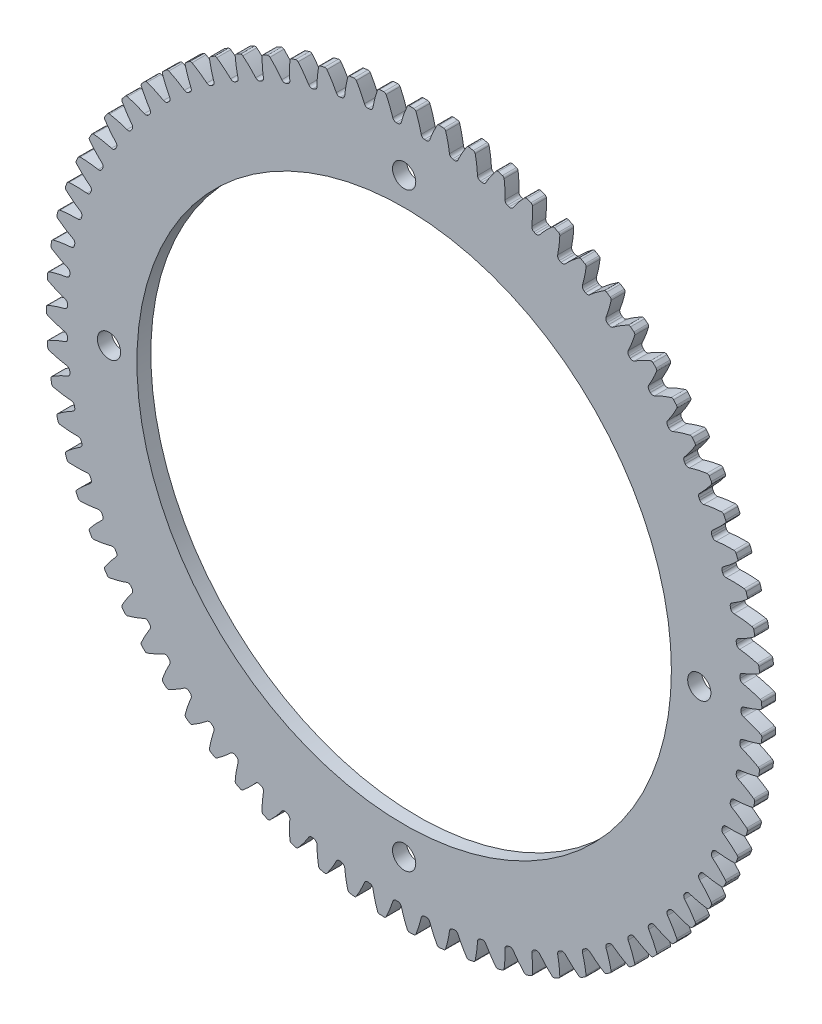
SolidWorks part; units mm, degrees
material "Thornel Mat VMA"
ref_plane "前视基准面" through (0, 0, 0) normal (0, 0, 1) x (1, 0, 0)
ref_plane "上视基准面" through (0, 0, 0) normal (0, 1, 0) x (1, 0, 0)
ref_plane "右视基准面" through (0, 0, 0) normal (1, 0, 0) x (0, 0, -1)
sketch "Model" plane through (0, 0, 0) normal (0, 0, 1) x (1, 0, 0)
  arc A0 (72.2612, 5.8798) -> (72.2457, 6.0666) centre (0, 0) ccw
  arc A1 (72.5, 0) -> (72.4998, 0.1875) centre (0, 0) ccw
  arc A2 (76.9325, 3.2244) -> (76.9114, 3.6924) centre (0, 0) ccw
  arc A3 (76.9507, 2.7563) -> (76.9325, 3.2244) centre (0, 0) ccw
  arc A4 (72.2612, 5.8798) -> (72.8687, 5.1964) centre (73.0187, 5.9414) ccw
  arc A5 (73.048, 0.9193) -> (72.4998, 0.1875) centre (73.2598, 0.1894) ccw
  arc A6 (76.9114, 3.6924) -> (76.5865, 4.137) centre (76.412, 3.6685) ccw
  arc A7 (76.6641, 2.2861) -> (76.9507, 2.7563) centre (76.451, 2.7384) ccw
  arc A8 (72.4998, -0.1875) -> (72.5, 0) centre (0, 0) ccw
  arc A9 (72.2457, -6.0666) -> (72.2612, -5.8798) centre (0, 0) ccw
  arc A10 (76.9325, -3.2244) -> (76.9507, -2.7563) centre (0, 0) ccw
  arc A11 (76.9114, -3.6924) -> (76.9325, -3.2244) centre (0, 0) ccw
  arc A12 (72.4998, -0.1875) -> (73.048, -0.9193) centre (73.2598, -0.1894) ccw
  arc A13 (72.8687, -5.1964) -> (72.2612, -5.8798) centre (73.0187, -5.9414) ccw
  arc A14 (76.9507, -2.7563) -> (76.6641, -2.2861) centre (76.451, -2.7384) ccw
  arc A15 (76.5865, -4.137) -> (76.9114, -3.6924) centre (76.412, -3.6685) ccw
  arc A16 (72.2298, -6.2534) -> (72.2457, -6.0666) centre (0, 0) ccw
  arc A17 (71.4847, -12.0907) -> (71.5157, -11.9059) centre (0, 0) ccw
  arc A18 (76.3928, -9.6507) -> (76.4501, -9.1857) centre (0, 0) ccw
  arc A19 (76.3327, -10.1153) -> (76.3928, -9.6507) centre (0, 0) ccw
  arc A20 (72.2298, -6.2534) -> (72.7148, -7.0286) centre (72.987, -6.319) ccw
  arc A21 (72.1783, -11.2757) -> (71.5157, -11.9059) centre (72.2654, -12.0307) ccw
  arc A22 (76.4501, -9.1857) -> (76.2039, -8.6931) centre (75.9537, -9.126) ccw
  arc A23 (75.9717, -10.5311) -> (76.3327, -10.1153) centre (75.837, -10.0496) ccw
  arc A24 (71.4532, -12.2755) -> (71.4847, -12.0907) centre (0, 0) ccw
  arc A25 (70.2223, -18.03) -> (70.2687, -17.8484) centre (0, 0) ccw
  arc A26 (75.3174, -16.0092) -> (75.4134, -15.5507) centre (0, 0) ccw
  arc A27 (75.2186, -16.4671) -> (75.3174, -16.0092) centre (0, 0) ccw
  arc A28 (71.4532, -12.2755) -> (71.8717, -13.0886) centre (72.2022, -12.4042) ccw
  arc A29 (70.9816, -17.2758) -> (70.2687, -17.8484) centre (71.0053, -18.0355) ccw
  arc A30 (75.4134, -15.5507) -> (75.2092, -15.0392) centre (74.9237, -15.4497) ccw
  arc A31 (74.824, -16.8513) -> (75.2186, -16.4671) centre (74.7301, -16.3602) ccw
  arc A32 (70.1754, -18.2115) -> (70.2223, -18.03) centre (0, 0) ccw
  arc A33 (68.4673, -23.8428) -> (68.5287, -23.6657) centre (0, 0) ccw
  arc A34 (73.7136, -22.2554) -> (73.8476, -21.8066) centre (0, 0) ccw
  arc A35 (73.5768, -22.7035) -> (73.7136, -22.2554) centre (0, 0) ccw
  arc A36 (70.1754, -18.2115) -> (70.5244, -19.0567) centre (70.9111, -18.4024) ccw
  arc A37 (69.2871, -23.1548) -> (68.5287, -23.6657) centre (69.2471, -23.9138) ccw
  arc A38 (73.8476, -21.8066) -> (73.687, -21.2798) centre (73.3681, -21.665) ccw
  arc A39 (73.1515, -23.0533) -> (73.5768, -22.7035) centre (73.0991, -22.5561) ccw
  arc A40 (68.4054, -24.0198) -> (68.4673, -23.8428) centre (0, 0) ccw
  arc A41 (66.232, -29.4884) -> (66.3081, -29.317) centre (0, 0) ccw
  arc A42 (71.5928, -28.3456) -> (71.7639, -27.9095) centre (0, 0) ccw
  arc A43 (71.419, -28.7806) -> (71.5928, -28.3456) centre (0, 0) ccw
  arc A44 (68.4054, -24.0198) -> (68.6824, -24.8912) centre (69.1225, -24.2716) ccw
  arc A45 (67.1066, -28.8714) -> (66.3081, -29.317) centre (67.0032, -29.6244) ccw
  arc A46 (71.7639, -27.9095) -> (71.6479, -27.3712) centre (71.2979, -27.7283) ccw
  arc A47 (70.9659, -29.0936) -> (71.419, -28.7806) centre (70.9552, -28.5938) ccw
  arc A48 (66.1556, -29.6596) -> (66.232, -29.4884) centre (0, 0) ccw
  arc A49 (63.5322, -34.9271) -> (63.6223, -34.7627) centre (0, 0) ccw
  arc A50 (68.9698, -34.2369) -> (69.1768, -33.8167) centre (0, 0) ccw
  arc A51 (68.7602, -34.6559) -> (68.9698, -34.2369) centre (0, 0) ccw
  arc A52 (66.1556, -29.6596) -> (66.3587, -30.5511) centre (66.8491, -29.9705) ccw
  arc A53 (64.4553, -34.3855) -> (63.6223, -34.7627) centre (64.2893, -35.1272) ccw
  arc A54 (69.1768, -33.8167) -> (69.1063, -33.2705) centre (68.7276, -33.5971) ccw
  arc A55 (68.2825, -34.9299) -> (68.7602, -34.6559) centre (68.3137, -34.4309) ccw
  arc A56 (63.4417, -35.0913) -> (63.5322, -34.9271) centre (0, 0) ccw
  arc A57 (60.3868, -40.1209) -> (60.4903, -39.9646) centre (0, 0) ccw
  arc A58 (65.863, -39.8881) -> (66.1045, -39.4866) centre (0, 0) ccw
  arc A59 (65.6191, -40.2881) -> (65.863, -39.8881) centre (0, 0) ccw
  arc A60 (63.4417, -35.0913) -> (63.5695, -35.9967) centre (64.1068, -35.4592) ccw
  arc A61 (61.3519, -39.6584) -> (60.4903, -39.9646) centre (61.1244, -40.3835) ccw
  arc A62 (66.1045, -39.4866) -> (66.0799, -38.9365) centre (65.6753, -39.2302) ccw
  arc A63 (65.1202, -40.5211) -> (65.6191, -40.2881) centre (65.193, -40.0264) ccw
  arc A64 (60.2828, -40.2769) -> (60.3868, -40.1209) centre (0, 0) ccw
  arc A65 (56.8178, -45.0332) -> (56.934, -44.8861) centre (0, 0) ccw
  arc A66 (62.2943, -45.2595) -> (62.5685, -44.8796) centre (0, 0) ccw
  arc A67 (62.0178, -45.6376) -> (62.2943, -45.2595) centre (0, 0) ccw
  arc A68 (60.2828, -40.2769) -> (60.3344, -41.1898) centre (60.9148, -40.6991) ccw
  arc A69 (57.8182, -44.6531) -> (56.934, -44.8861) centre (57.5309, -45.3567) ccw
  arc A70 (62.5685, -44.8796) -> (62.59, -44.3294) centre (62.1622, -44.5882) ccw
  arc A71 (61.5011, -45.8281) -> (62.0178, -45.6376) centre (61.6151, -45.3413) ccw
  arc A72 (56.7011, -45.18) -> (56.8178, -45.0332) centre (0, 0) ccw
  arc A73 (52.8502, -49.6297) -> (52.9784, -49.4928) centre (0, 0) ccw
  arc A74 (58.2886, -50.3134) -> (58.5937, -49.9578) centre (0, 0) ccw
  arc A75 (57.9814, -50.6671) -> (58.2886, -50.3134) centre (0, 0) ccw
  arc A76 (56.7011, -45.18) -> (56.6762, -46.094) centre (57.2955, -45.6536) ccw
  arc A77 (53.879, -49.3346) -> (52.9784, -49.4928) centre (53.5337, -50.0117) ccw
  arc A78 (58.5937, -49.9578) -> (58.6611, -49.4113) centre (58.2132, -49.6334) ccw
  arc A79 (57.4506, -50.8137) -> (57.9814, -50.6671) centre (57.6049, -50.3381) ccw
  arc A80 (52.7217, -49.7662) -> (52.8502, -49.6297) centre (0, 0) ccw
  arc A81 (48.512, -53.878) -> (48.6511, -53.7524) centre (0, 0) ccw
  arc A82 (53.8741, -55.0144) -> (54.2078, -54.6856) centre (0, 0) ccw
  arc A83 (53.5384, -55.3412) -> (53.8741, -55.0144) centre (0, 0) ccw
  arc A84 (52.7217, -49.7662) -> (52.6203, -50.6749) centre (53.2744, -50.2878) ccw
  arc A85 (49.5618, -53.6701) -> (48.6511, -53.7524) centre (49.1611, -54.3159) ccw
  arc A86 (54.2078, -54.6856) -> (54.3208, -54.1466) centre (53.8558, -54.3305) ccw
  arc A87 (52.9971, -55.4428) -> (53.5384, -55.3412) centre (53.1907, -54.9818) ccw
  arc A88 (48.3725, -54.0033) -> (48.512, -53.878) centre (0, 0) ccw
  arc A89 (43.8334, -57.7484) -> (43.9826, -57.6349) centre (0, 0) ccw
  arc A90 (49.0816, -59.3295) -> (49.4417, -59.0298) centre (0, 0) ccw
  arc A91 (48.7198, -59.627) -> (49.0816, -59.3295) centre (0, 0) ccw
  arc A92 (48.3725, -54.0033) -> (48.1954, -54.9004) centre (48.8796, -54.5694) ccw
  arc A93 (44.897, -57.6291) -> (43.9826, -57.6349) centre (44.4437, -58.2391) ccw
  arc A94 (49.4417, -59.0298) -> (49.5994, -58.5022) centre (49.1207, -58.6465) ccw
  arc A95 (48.1719, -59.6831) -> (48.7198, -59.627) centre (48.4034, -59.2399) ccw
  arc A96 (43.684, -57.8616) -> (43.8334, -57.7484) centre (0, 0) ccw
  arc A97 (38.8474, -61.2138) -> (39.0056, -61.1131) centre (0, 0) ccw
  arc A98 (43.9449, -63.2285) -> (44.3288, -62.96) centre (0, 0) ccw
  arc A99 (43.5594, -63.4947) -> (43.9449, -63.2285) centre (0, 0) ccw
  arc A100 (43.684, -57.8616) -> (43.4325, -58.7407) centre (44.1419, -58.4681) ccw
  arc A101 (39.9173, -61.1838) -> (39.0056, -61.1131) centre (39.4145, -61.7538) ccw
  arc A102 (44.3288, -62.96) -> (44.5301, -62.4474) centre (44.041, -62.5511) ccw
  arc A103 (43.0089, -63.5047) -> (43.5594, -63.4947) centre (43.2766, -63.0824) ccw
  arc A104 (38.689, -61.314) -> (38.8474, -61.2138) centre (0, 0) ccw
  arc A105 (33.589, -64.2498) -> (33.755, -64.1627) centre (0, 0) ccw
  arc A106 (38.5, -66.684) -> (38.905, -66.4485) centre (0, 0) ccw
  arc A107 (38.0936, -66.917) -> (38.5, -66.684) centre (0, 0) ccw
  arc A108 (38.689, -61.314) -> (38.3648, -62.169) centre (39.0946, -61.9568) ccw
  arc A109 (34.6575, -64.3094) -> (33.755, -64.1627) centre (34.1088, -64.8353) ccw
  arc A110 (38.905, -66.4485) -> (39.1485, -65.9545) centre (38.6524, -66.017) ccw
  arc A111 (37.5441, -66.8808) -> (38.0936, -66.917) centre (37.8462, -66.4824) ccw
  arc A112 (33.4227, -64.3364) -> (33.589, -64.2498) centre (0, 0) ccw
  arc A113 (28.0949, -66.8351) -> (28.2676, -66.7622) centre (0, 0) ccw
  arc A114 (32.785, -69.6717) -> (33.2083, -69.4709) centre (0, 0) ccw
  arc A115 (32.3605, -69.8699) -> (32.785, -69.6717) centre (0, 0) ccw
  arc A116 (33.4227, -64.3364) -> (33.0281, -65.1613) centre (33.7731, -65.0108) ccw
  arc A117 (29.1547, -66.984) -> (28.2676, -66.7622) centre (28.5639, -67.4621) ccw
  arc A118 (33.2083, -69.4709) -> (33.4922, -68.9991) centre (32.9927, -69.0198) ccw
  arc A119 (31.816, -69.7879) -> (32.3605, -69.8699) centre (32.1504, -69.4162) ccw
  arc A120 (27.922, -66.9075) -> (28.0949, -66.8351) centre (0, 0) ccw
  arc A121 (22.4037, -68.9516) -> (22.582, -68.8934) centre (0, 0) ccw
  arc A122 (26.84, -72.1707) -> (27.2786, -72.0061) centre (0, 0) ccw
  arc A123 (26.4005, -72.3327) -> (26.84, -72.1707) centre (0, 0) ccw
  arc A124 (27.922, -66.9075) -> (27.4597, -67.6965) centre (28.2147, -67.6089) ccw
  arc A125 (23.4474, -69.1886) -> (22.582, -68.8934) centre (22.8187, -69.6156) ccw
  arc A126 (27.2786, -72.0061) -> (27.6011, -71.5597) centre (27.1015, -71.5385) ccw
  arc A127 (25.8647, -72.2054) -> (26.4005, -72.3327) centre (26.229, -71.863) ccw
  arc A128 (22.2254, -69.0093) -> (22.4037, -68.9516) centre (0, 0) ccw
  arc A129 (16.5554, -70.5845) -> (16.7379, -70.5414) centre (0, 0) ccw
  arc A130 (20.7068, -74.1635) -> (21.1577, -74.0362) centre (0, 0) ccw
  arc A131 (20.2552, -74.2881) -> (20.7068, -74.1635) centre (0, 0) ccw
  arc A132 (22.2254, -69.0093) -> (21.6987, -69.7568) centre (22.4583, -69.7327) ccw
  arc A133 (17.5756, -70.908) -> (16.7379, -70.5414) centre (16.9134, -71.2809) ccw
  arc A134 (21.1577, -74.0362) -> (21.5163, -73.6183) centre (21.0203, -73.5554) ccw
  arc A135 (19.732, -74.1165) -> (20.2552, -74.2881) centre (20.1237, -73.8057) ccw
  arc A136 (16.3729, -70.627) -> (16.5554, -70.5845) centre (0, 0) ccw
  arc A137 (10.591, -71.7222) -> (10.7764, -71.6946) centre (0, 0) ccw
  arc A138 (14.4284, -75.6361) -> (14.8883, -75.5469) centre (0, 0) ccw
  arc A139 (13.9679, -75.7225) -> (14.4284, -75.6361) centre (0, 0) ccw
  arc A140 (16.3729, -70.627) -> (15.7855, -71.3279) centre (16.5445, -71.3674) ccw
  arc A141 (11.5805, -72.13) -> (10.7764, -71.6946) centre (10.8894, -72.4462) ccw
  arc A142 (14.8883, -75.5469) -> (15.2806, -75.1605) centre (14.7916, -75.0564) ccw
  arc A143 (13.4609, -75.5077) -> (13.9679, -75.7225) centre (13.8772, -75.2308) ccw
  arc A144 (10.4055, -71.7494) -> (10.591, -71.7222) centre (0, 0) ccw
  arc A145 (4.5523, -72.3569) -> (4.7394, -72.3449) centre (0, 0) ccw
  arc A146 (8.0487, -76.5782) -> (8.5145, -76.5278) centre (0, 0) ccw
  arc A147 (7.5826, -76.6257) -> (8.0487, -76.5782) centre (0, 0) ccw
  arc A148 (10.4055, -71.7494) -> (9.7616, -72.3986) centre (10.5146, -72.5015) ccw
  arc A149 (5.5042, -72.8461) -> (4.7394, -72.3449) centre (4.7891, -73.1033) ccw
  arc A150 (8.5145, -76.5278) -> (8.9378, -76.1756) centre (8.4592, -76.0309) ccw
  arc A151 (7.0953, -76.3692) -> (7.5826, -76.6257) centre (7.5334, -76.1282) ccw
  arc A152 (4.3652, -72.3685) -> (4.5523, -72.3569) centre (0, 0) ccw
  arc A153 (-1.5183, -72.4841) -> (-1.3309, -72.4878) centre (0, 0) ccw
  arc A154 (1.6126, -76.9831) -> (2.0809, -76.9719) centre (0, 0) ccw
  arc A155 (1.1442, -76.9915) -> (1.6126, -76.9831) centre (0, 0) ccw
  arc A156 (4.3652, -72.3685) -> (3.6692, -72.9615) centre (4.411, -73.1271) ccw
  arc A157 (-0.6107, -73.0512) -> (-1.3309, -72.4878) centre (-1.3448, -73.2477) ccw
  arc A158 (2.0809, -76.9719) -> (2.5322, -76.6563) centre (2.0674, -76.4721) ccw
  arc A159 (0.68, -76.6951) -> (1.1442, -76.9915) centre (1.1367, -76.4916) ccw
  arc A160 (-1.7057, -72.4799) -> (-1.5183, -72.4841) centre (0, 0) ccw
  arc A161 (-7.5783, -72.1028) -> (-7.3918, -72.1222) centre (0, 0) ccw
  arc A162 (-4.8349, -76.8481) -> (-4.3672, -76.8761) centre (0, 0) ccw
  arc A163 (-5.3023, -76.8172) -> (-4.8349, -76.8481) centre (0, 0) ccw
  arc A164 (-1.7057, -72.4799) -> (-2.4489, -73.0127) centre (-1.7236, -73.2397) ccw
  arc A165 (-6.7213, -72.7439) -> (-7.3918, -72.1222) centre (-7.4693, -72.8782) ccw
  arc A166 (-4.3672, -76.8761) -> (-3.8911, -76.5994) centre (-4.3389, -76.3769) ccw
  arc A167 (-5.74, -76.483) -> (-5.3023, -76.8172) centre (-5.2679, -76.3184) ccw
  arc A168 (-7.7647, -72.083) -> (-7.5783, -72.1028) centre (0, 0) ccw
  arc A169 (-13.5851, -71.2158) -> (-13.401, -71.2507) centre (0, 0) ccw
  arc A170 (-11.2484, -76.174) -> (-10.7847, -76.241) centre (0, 0) ccw
  arc A171 (-11.7116, -76.1041) -> (-11.2484, -76.174) centre (0, 0) ccw
  arc A172 (-7.7647, -72.083) -> (-8.5499, -72.5517) centre (-7.8461, -72.8386) ccw
  arc A173 (-12.7848, -71.9263) -> (-13.401, -71.2507) centre (-13.5414, -71.9976) ccw
  arc A174 (-10.7847, -76.241) -> (-10.2871, -76.0051) centre (-10.7147, -75.7459) ccw
  arc A175 (-12.1198, -75.7345) -> (-11.7116, -76.1041) centre (-11.6356, -75.6099) ccw
  arc A176 (-13.7692, -71.1805) -> (-13.5851, -71.2158) centre (0, 0) ccw
  arc A177 (-19.4967, -69.8293) -> (-19.3161, -69.8795) centre (0, 0) ccw
  arc A178 (-17.583, -74.9656) -> (-17.1266, -75.0712) centre (0, 0) ccw
  arc A179 (-18.0388, -74.8572) -> (-17.583, -74.9656) centre (0, 0) ccw
  arc A180 (-13.7692, -71.1805) -> (-14.5909, -71.5818) centre (-13.9136, -71.9266) ccw
  arc A181 (-18.7586, -70.6043) -> (-19.3161, -69.8795) centre (-19.5185, -70.612) ccw
  arc A182 (-17.1266, -75.0712) -> (-16.611, -74.8778) centre (-17.0154, -74.5837) ccw
  arc A183 (-18.4146, -74.4547) -> (-18.0388, -74.8572) centre (-17.9217, -74.3711) ccw
  arc A184 (-19.6772, -69.7786) -> (-19.4967, -69.8293) centre (0, 0) ccw
  arc A185 (-25.2715, -67.9529) -> (-25.0957, -68.0181) centre (0, 0) ccw
  arc A186 (-23.7943, -73.2314) -> (-23.3483, -73.3748) centre (0, 0) ccw
  arc A187 (-24.2394, -73.0852) -> (-23.7943, -73.2314) centre (0, 0) ccw
  arc A188 (-19.6772, -69.7786) -> (-20.5295, -70.1098) centre (-19.8835, -70.5101) ccw
  arc A189 (-24.6008, -68.787) -> (-25.0957, -68.0181) centre (-25.3587, -68.7311) ccw
  arc A190 (-23.3483, -73.3748) -> (-22.8183, -73.2252) centre (-23.1967, -72.8983) ccw
  arc A191 (-24.5802, -72.6527) -> (-24.2394, -73.0852) centre (-24.082, -72.6106) ccw
  arc A192 (-25.4471, -67.8874) -> (-25.2715, -67.9529) centre (0, 0) ccw
  arc A193 (-30.869, -65.6) -> (-30.6993, -65.6796) centre (0, 0) ccw
  arc A194 (-29.8387, -70.9835) -> (-29.4063, -71.1637) centre (0, 0) ccw
  arc A195 (-30.27, -70.8006) -> (-29.8387, -70.9835) centre (0, 0) ccw
  arc A196 (-25.4471, -67.8874) -> (-26.3241, -68.1461) centre (-25.7139, -68.599) ccw
  arc A197 (-30.2705, -66.4872) -> (-30.6993, -65.6796) centre (-31.0211, -66.3681) ccw
  arc A198 (-29.4063, -71.1637) -> (-28.8656, -71.059) centre (-29.2153, -70.7016) ccw
  arc A199 (-30.5735, -70.3411) -> (-30.27, -70.8006) centre (-30.0735, -70.3409) ccw
  arc A200 (-31.0385, -65.5199) -> (-30.869, -65.6) centre (0, 0) ccw
  arc A201 (-36.25, -62.7868) -> (-36.0875, -62.8804) centre (0, 0) ccw
  arc A202 (-35.6738, -68.2377) -> (-35.258, -68.4535) centre (0, 0) ccw
  arc A203 (-36.0883, -68.0194) -> (-35.6738, -68.2377) centre (0, 0) ccw
  arc A204 (-31.0385, -65.5199) -> (-31.9341, -65.7043) centre (-31.3639, -66.2068) ccw
  arc A205 (-35.7278, -63.721) -> (-36.0875, -62.8804) centre (-36.4658, -63.5395) ccw
  arc A206 (-35.258, -68.4535) -> (-34.7105, -68.3943) centre (-35.029, -68.009) ccw
  arc A207 (-36.3522, -67.5361) -> (-36.0883, -68.0194) centre (-35.854, -67.5777) ccw
  arc A208 (-36.4122, -62.6929) -> (-36.25, -62.7868) centre (0, 0) ccw
  arc A209 (-41.3767, -59.5333) -> (-41.2227, -59.6401) centre (0, 0) ccw
  arc A210 (-41.2587, -65.0133) -> (-40.8624, -65.2631) centre (0, 0) ccw
  arc A211 (-41.6534, -64.761) -> (-41.2587, -65.0133) centre (0, 0) ccw
  arc A212 (-36.4122, -62.6929) -> (-37.3201, -62.8017) centre (-36.7939, -63.3501) ccw
  arc A213 (-40.9346, -60.5079) -> (-41.2227, -59.6401) centre (-41.6548, -60.2653) ccw
  arc A214 (-40.8624, -65.2631) -> (-40.3118, -65.25) centre (-40.597, -64.8393) ccw
  arc A215 (-41.876, -64.2573) -> (-41.6534, -64.761) centre (-41.383, -64.3405) ccw
  arc A216 (-41.5305, -59.4261) -> (-41.3767, -59.5333) centre (0, 0) ccw
  arc A217 (-46.2132, -55.8622) -> (-46.0686, -55.9815) centre (0, 0) ccw
  arc A218 (-46.5541, -61.3328) -> (-46.1801, -61.6149) centre (0, 0) ccw
  arc A219 (-46.9264, -61.0484) -> (-46.5541, -61.3328) centre (0, 0) ccw
  arc A220 (-41.5305, -59.4261) -> (-42.4444, -59.4586) centre (-41.9659, -60.0491) ccw
  arc A221 (-45.8542, -56.8704) -> (-46.0686, -55.9815) centre (-46.5516, -56.5684) ccw
  arc A222 (-46.1801, -61.6149) -> (-45.6304, -61.6479) centre (-45.8802, -61.2148) ccw
  arc A223 (-47.1061, -60.5279) -> (-46.9264, -61.0484) centre (-46.6217, -60.652) ccw
  arc A224 (-46.3575, -55.7425) -> (-46.2132, -55.8622) centre (0, 0) ccw
  arc A225 (-50.7256, -51.7993) -> (-50.5915, -51.9303) centre (0, 0) ccw
  arc A226 (-51.5231, -57.2222) -> (-51.174, -57.5346) centre (0, 0) ccw
  arc A227 (-51.8702, -56.9076) -> (-51.5231, -57.2222) centre (0, 0) ccw
  arc A228 (-46.3575, -55.7425) -> (-47.2709, -55.6984) centre (-46.8435, -56.3269) ccw
  arc A229 (-50.4521, -52.834) -> (-50.5915, -51.9303) centre (-51.1218, -52.4746) ccw
  arc A230 (-51.174, -57.5346) -> (-50.629, -57.6135) centre (-50.8417, -57.161) ccw
  arc A231 (-52.0057, -56.3739) -> (-51.8702, -56.9076) centre (-51.5334, -56.5381) ccw
  arc A232 (-50.8594, -51.6679) -> (-50.7256, -51.7993) centre (0, 0) ccw
  arc A233 (-54.8821, -47.373) -> (-54.7595, -47.5147) centre (0, 0) ccw
  arc A234 (-56.1306, -52.7101) -> (-55.8089, -53.0507) centre (0, 0) ccw
  arc A235 (-56.4502, -52.3676) -> (-56.1306, -52.7101) centre (0, 0) ccw
  arc A236 (-50.8594, -51.6679) -> (-51.7658, -51.5476) centre (-51.3925, -52.2096) ccw
  arc A237 (-54.6962, -48.427) -> (-54.7595, -47.5147) centre (-55.3335, -48.0128) ccw
  arc A238 (-55.8089, -53.0507) -> (-55.2724, -53.1749) centre (-55.4465, -52.7062) ccw
  arc A239 (-56.5405, -51.8244) -> (-56.4502, -52.3676) centre (-56.0837, -52.0276) ccw
  arc A240 (-55.0045, -47.2309) -> (-54.8821, -47.373) centre (0, 0) ccw
  arc A241 (-58.6537, -42.6144) -> (-58.5433, -42.766) centre (0, 0) ccw
  arc A242 (-60.3444, -47.8284) -> (-60.0523, -48.1946) centre (0, 0) ccw
  arc A243 (-60.6343, -47.4604) -> (-60.3444, -47.8284) centre (0, 0) ccw
  arc A244 (-55.0045, -47.2309) -> (-55.8976, -47.0351) centre (-55.5811, -47.726) ccw
  arc A245 (-58.5567, -43.6803) -> (-58.5433, -42.766) centre (-59.157, -43.2143) ccw
  arc A246 (-60.0523, -48.1946) -> (-59.5281, -48.3633) centre (-59.6623, -47.8817) ccw
  arc A247 (-60.6788, -46.9115) -> (-60.6343, -47.4604) centre (-60.2405, -47.1522) ccw
  arc A248 (-58.7637, -42.4626) -> (-58.6537, -42.6144) centre (0, 0) ccw
  arc A249 (-62.0139, -37.557) -> (-61.9166, -37.7172) centre (0, 0) ccw
  arc A250 (-64.1349, -42.6111) -> (-63.8745, -43.0006) centre (0, 0) ccw
  arc A251 (-64.393, -42.2202) -> (-64.1349, -42.6111) centre (0, 0) ccw
  arc A252 (-58.7637, -42.4626) -> (-59.6374, -42.1928) centre (-59.3797, -42.9077) ccw
  arc A253 (-62.0064, -38.6272) -> (-61.9166, -37.7172) centre (-62.5656, -38.1126) ccw
  arc A254 (-63.8745, -43.0006) -> (-63.3662, -43.2125) centre (-63.4597, -42.7213) ccw
  arc A255 (-64.3914, -41.6695) -> (-64.393, -42.2202) centre (-63.9749, -41.946) ccw
  arc A256 (-62.1108, -37.3965) -> (-62.0139, -37.557) centre (0, 0) ccw
  arc A257 (-64.9391, -32.2361) -> (-64.8555, -32.4039) centre (0, 0) ccw
  arc A258 (-67.4756, -37.095) -> (-67.2487, -37.5049) centre (0, 0) ccw
  arc A259 (-67.7001, -36.6838) -> (-67.4756, -37.095) centre (0, 0) ccw
  arc A260 (-62.1108, -37.3965) -> (-62.9588, -37.0545) centre (-62.7619, -37.7885) ccw
  arc A261 (-65.0211, -33.3031) -> (-64.8555, -32.4039) centre (-65.5354, -32.7435) ccw
  arc A262 (-67.2487, -37.5049) -> (-66.7599, -37.7586) centre (-66.812, -37.2613) ccw
  arc A263 (-67.6524, -36.1352) -> (-67.7001, -36.6838) centre (-67.2604, -36.4456) ccw
  arc A264 (-65.0222, -32.068) -> (-64.9391, -32.2361) centre (0, 0) ccw
  arc A265 (-67.4088, -26.689) -> (-67.3396, -26.8632) centre (0, 0) ccw
  arc A266 (-70.343, -31.3187) -> (-70.1512, -31.7461) centre (0, 0) ccw
  arc A267 (-70.5322, -30.8902) -> (-70.343, -31.3187) centre (0, 0) ccw
  arc A268 (-65.0222, -32.068) -> (-65.8387, -31.6562) centre (-65.7039, -32.4042) ccw
  arc A269 (-67.5798, -27.7455) -> (-67.3396, -26.8632) centre (-68.0455, -27.1448) ccw
  arc A270 (-70.1512, -31.7461) -> (-69.6854, -32.0399) centre (-69.6956, -31.54) ccw
  arc A271 (-70.4389, -30.3475) -> (-70.5322, -30.8902) centre (-70.0742, -30.6896) ccw
  arc A272 (-67.4776, -26.5146) -> (-67.4088, -26.689) centre (0, 0) ccw
  arc A273 (-69.4057, -20.9548) -> (-69.3512, -21.1342) centre (0, 0) ccw
  arc A274 (-72.717, -25.3227) -> (-72.5616, -25.7647) centre (0, 0) ccw
  arc A275 (-72.8697, -24.8798) -> (-72.717, -25.3227) centre (0, 0) ccw
  arc A276 (-67.4776, -26.5146) -> (-68.2567, -26.036) centre (-68.1849, -26.7926) ccw
  arc A277 (-69.6645, -21.9933) -> (-69.3512, -21.1342) centre (-70.0782, -21.3557) ccw
  arc A278 (-72.5616, -25.7647) -> (-72.122, -26.0964) centre (-72.0904, -25.5974) ccw
  arc A279 (-72.7312, -24.3469) -> (-72.8697, -24.8798) centre (-72.3965, -24.7183) ccw
  arc A280 (-69.4596, -20.7753) -> (-69.4057, -20.9548) centre (0, 0) ccw
  arc A281 (-70.9157, -15.0736) -> (-70.8765, -15.2569) centre (0, 0) ccw
  arc A282 (-74.5809, -19.1491) -> (-74.463, -19.6025) centre (0, 0) ccw
  arc A283 (-74.696, -18.695) -> (-74.5809, -19.1491) centre (0, 0) ccw
  arc A284 (-69.4596, -20.7753) -> (-70.1959, -20.2331) centre (-70.1877, -20.993) ccw
  arc A285 (-71.2605, -16.0868) -> (-70.8765, -15.2569) centre (-71.6195, -15.4169) ccw
  arc A286 (-74.463, -19.6025) -> (-74.0527, -19.9698) centre (-73.9795, -19.4752) ccw
  arc A287 (-74.5135, -18.1755) -> (-74.696, -18.695) centre (-74.211, -18.5736) ccw
  arc A288 (-70.9544, -14.8902) -> (-70.9157, -15.0736) centre (0, 0) ccw
  arc A289 (-71.9283, -9.0867) -> (-71.9046, -9.2726) centre (0, 0) ccw
  arc A290 (-75.9217, -12.8412) -> (-75.8422, -13.3029) centre (0, 0) ccw
  arc A291 (-75.9984, -12.379) -> (-75.9217, -12.8412) centre (0, 0) ccw
  arc A292 (-70.9544, -14.8902) -> (-71.6428, -14.2883) centre (-71.6982, -15.0463) ccw
  arc A293 (-72.3567, -10.0674) -> (-71.9046, -9.2726) centre (-72.6583, -9.3698) ccw
  arc A294 (-75.8422, -13.3029) -> (-75.4641, -13.7032) centre (-75.3497, -13.2165) ccw
  arc A295 (-75.773, -11.8766) -> (-75.9984, -12.379) centre (-75.5049, -12.2987) ccw
  arc A296 (-71.9516, -8.9006) -> (-71.9283, -9.0867) centre (0, 0) ccw
  arc A297 (-72.4364, -3.036) -> (-72.4283, -3.2233) centre (0, 0) ccw
  arc A298 (-76.73, -6.4432) -> (-76.6893, -6.9099) centre (0, 0) ccw
  arc A299 (-76.7677, -5.9762) -> (-76.73, -6.4432) centre (0, 0) ccw
  arc A300 (-71.9516, -8.9006) -> (-72.5872, -8.2433) centre (-72.7058, -8.9939) ccw
  arc A301 (-72.9454, -3.9774) -> (-72.4283, -3.2233) centre (-73.1876, -3.2571) ccw
  arc A302 (-76.6893, -6.9099) -> (-76.3461, -7.3405) centre (-76.1913, -6.865) ccw
  arc A303 (-76.5011, -5.4944) -> (-76.7677, -5.9762) centre (-76.2692, -5.9374) ccw
  arc A304 (-72.444, -2.8487) -> (-72.4364, -3.036) centre (0, 0) ccw
  arc A305 (-72.4364, 3.036) -> (-72.444, 2.8487) centre (0, 0) ccw
  arc A306 (-77, 0) -> (-76.9986, -0.4685) centre (0, 0) ccw
  arc A307 (-76.9986, 0.4685) -> (-77, 0) centre (0, 0) ccw
  arc A308 (-72.444, -2.8487) -> (-73.0224, -2.1404) centre (-73.2034, -2.8785) ccw
  arc A309 (-73.0224, 2.1404) -> (-72.444, 2.8487) centre (-73.2034, 2.8785) ccw
  arc A310 (-76.9986, -0.4685) -> (-76.6925, -0.9263) centre (-76.4986, -0.4654) ccw
  arc A311 (-76.6925, 0.9263) -> (-76.9986, 0.4685) centre (-76.4986, 0.4654) ccw
  arc A312 (-72.4283, 3.2233) -> (-72.4364, 3.036) centre (0, 0) ccw
  arc A313 (-71.9283, 9.0867) -> (-71.9516, 8.9006) centre (0, 0) ccw
  arc A314 (-76.73, 6.4432) -> (-76.7677, 5.9762) centre (0, 0) ccw
  arc A315 (-76.6893, 6.9099) -> (-76.73, 6.4432) centre (0, 0) ccw
  arc A316 (-72.4283, 3.2233) -> (-72.9454, 3.9774) centre (-73.1876, 3.2571) ccw
  arc A317 (-72.5872, 8.2433) -> (-71.9516, 8.9006) centre (-72.7058, 8.9939) ccw
  arc A318 (-76.7677, 5.9762) -> (-76.5011, 5.4944) centre (-76.2692, 5.9374) ccw
  arc A319 (-76.3461, 7.3405) -> (-76.6893, 6.9099) centre (-76.1913, 6.865) ccw
  arc A320 (-71.9046, 9.2726) -> (-71.9283, 9.0867) centre (0, 0) ccw
  arc A321 (-70.9157, 15.0736) -> (-70.9544, 14.8902) centre (0, 0) ccw
  arc A322 (-75.9217, 12.8412) -> (-75.9984, 12.379) centre (0, 0) ccw
  arc A323 (-75.8422, 13.3029) -> (-75.9217, 12.8412) centre (0, 0) ccw
  arc A324 (-71.9046, 9.2726) -> (-72.3567, 10.0674) centre (-72.6583, 9.3698) ccw
  arc A325 (-71.6428, 14.2883) -> (-70.9544, 14.8902) centre (-71.6982, 15.0463) ccw
  arc A326 (-75.9984, 12.379) -> (-75.773, 11.8766) centre (-75.5049, 12.2987) ccw
  arc A327 (-75.4641, 13.7032) -> (-75.8422, 13.3029) centre (-75.3497, 13.2165) ccw
  arc A328 (-70.8765, 15.2569) -> (-70.9157, 15.0736) centre (0, 0) ccw
  arc A329 (-69.4057, 20.9548) -> (-69.4596, 20.7753) centre (0, 0) ccw
  arc A330 (-74.5809, 19.1491) -> (-74.696, 18.695) centre (0, 0) ccw
  arc A331 (-74.463, 19.6025) -> (-74.5809, 19.1491) centre (0, 0) ccw
  arc A332 (-70.8765, 15.2569) -> (-71.2605, 16.0868) centre (-71.6195, 15.4169) ccw
  arc A333 (-70.1959, 20.2331) -> (-69.4596, 20.7753) centre (-70.1877, 20.993) ccw
  arc A334 (-74.696, 18.695) -> (-74.5135, 18.1755) centre (-74.211, 18.5736) ccw
  arc A335 (-74.0527, 19.9698) -> (-74.463, 19.6025) centre (-73.9795, 19.4752) ccw
  arc A336 (-69.3512, 21.1342) -> (-69.4057, 20.9548) centre (0, 0) ccw
  arc A337 (-67.4088, 26.689) -> (-67.4776, 26.5146) centre (0, 0) ccw
  arc A338 (-72.717, 25.3227) -> (-72.8697, 24.8798) centre (0, 0) ccw
  arc A339 (-72.5616, 25.7647) -> (-72.717, 25.3227) centre (0, 0) ccw
  arc A340 (-69.3512, 21.1342) -> (-69.6645, 21.9933) centre (-70.0782, 21.3557) ccw
  arc A341 (-68.2567, 26.036) -> (-67.4776, 26.5146) centre (-68.1849, 26.7926) ccw
  arc A342 (-72.8697, 24.8798) -> (-72.7312, 24.3469) centre (-72.3965, 24.7183) ccw
  arc A343 (-72.122, 26.0964) -> (-72.5616, 25.7647) centre (-72.0904, 25.5974) ccw
  arc A344 (-67.3396, 26.8632) -> (-67.4088, 26.689) centre (0, 0) ccw
  arc A345 (-64.9391, 32.2361) -> (-65.0222, 32.068) centre (0, 0) ccw
  arc A346 (-70.343, 31.3187) -> (-70.5322, 30.8902) centre (0, 0) ccw
  arc A347 (-70.1512, 31.7461) -> (-70.343, 31.3187) centre (0, 0) ccw
  arc A348 (-67.3396, 26.8632) -> (-67.5798, 27.7455) centre (-68.0455, 27.1448) ccw
  arc A349 (-65.8387, 31.6562) -> (-65.0222, 32.068) centre (-65.7039, 32.4042) ccw
  arc A350 (-70.5322, 30.8902) -> (-70.4389, 30.3475) centre (-70.0742, 30.6896) ccw
  arc A351 (-69.6854, 32.0399) -> (-70.1512, 31.7461) centre (-69.6956, 31.54) ccw
  arc A352 (-64.8555, 32.4039) -> (-64.9391, 32.2361) centre (0, 0) ccw
  arc A353 (-62.0139, 37.557) -> (-62.1108, 37.3965) centre (0, 0) ccw
  arc A354 (-67.4756, 37.095) -> (-67.7001, 36.6838) centre (0, 0) ccw
  arc A355 (-67.2487, 37.5049) -> (-67.4756, 37.095) centre (0, 0) ccw
  arc A356 (-64.8555, 32.4039) -> (-65.0211, 33.3031) centre (-65.5354, 32.7435) ccw
  arc A357 (-62.9588, 37.0545) -> (-62.1108, 37.3965) centre (-62.7619, 37.7885) ccw
  arc A358 (-67.7001, 36.6838) -> (-67.6524, 36.1352) centre (-67.2604, 36.4456) ccw
  arc A359 (-66.7599, 37.7586) -> (-67.2487, 37.5049) centre (-66.812, 37.2613) ccw
  arc A360 (-61.9166, 37.7172) -> (-62.0139, 37.557) centre (0, 0) ccw
  arc A361 (-58.6537, 42.6144) -> (-58.7637, 42.4626) centre (0, 0) ccw
  arc A362 (-64.1349, 42.6111) -> (-64.393, 42.2202) centre (0, 0) ccw
  arc A363 (-63.8745, 43.0006) -> (-64.1349, 42.6111) centre (0, 0) ccw
  arc A364 (-61.9166, 37.7172) -> (-62.0064, 38.6272) centre (-62.5656, 38.1126) ccw
  arc A365 (-59.6374, 42.1928) -> (-58.7637, 42.4626) centre (-59.3797, 42.9077) ccw
  arc A366 (-64.393, 42.2202) -> (-64.3914, 41.6695) centre (-63.9749, 41.946) ccw
  arc A367 (-63.3662, 43.2125) -> (-63.8745, 43.0006) centre (-63.4597, 42.7213) ccw
  arc A368 (-58.5433, 42.766) -> (-58.6537, 42.6144) centre (0, 0) ccw
  arc A369 (-54.8821, 47.373) -> (-55.0045, 47.2309) centre (0, 0) ccw
  arc A370 (-60.3444, 47.8284) -> (-60.6343, 47.4604) centre (0, 0) ccw
  arc A371 (-60.0523, 48.1946) -> (-60.3444, 47.8284) centre (0, 0) ccw
  arc A372 (-58.5433, 42.766) -> (-58.5567, 43.6803) centre (-59.157, 43.2143) ccw
  arc A373 (-55.8976, 47.0351) -> (-55.0045, 47.2309) centre (-55.5811, 47.726) ccw
  arc A374 (-60.6343, 47.4604) -> (-60.6788, 46.9115) centre (-60.2405, 47.1522) ccw
  arc A375 (-59.5281, 48.3633) -> (-60.0523, 48.1946) centre (-59.6623, 47.8817) ccw
  arc A376 (-54.7595, 47.5147) -> (-54.8821, 47.373) centre (0, 0) ccw
  arc A377 (-50.7256, 51.7993) -> (-50.8594, 51.6679) centre (0, 0) ccw
  arc A378 (-56.1306, 52.7101) -> (-56.4502, 52.3676) centre (0, 0) ccw
  arc A379 (-55.8089, 53.0507) -> (-56.1306, 52.7101) centre (0, 0) ccw
  arc A380 (-54.7595, 47.5147) -> (-54.6962, 48.427) centre (-55.3335, 48.0128) ccw
  arc A381 (-51.7658, 51.5476) -> (-50.8594, 51.6679) centre (-51.3925, 52.2096) ccw
  arc A382 (-56.4502, 52.3676) -> (-56.5405, 51.8244) centre (-56.0837, 52.0276) ccw
  arc A383 (-55.2724, 53.1749) -> (-55.8089, 53.0507) centre (-55.4465, 52.7062) ccw
  arc A384 (-50.5915, 51.9303) -> (-50.7256, 51.7993) centre (0, 0) ccw
  arc A385 (-46.2132, 55.8622) -> (-46.3575, 55.7425) centre (0, 0) ccw
  arc A386 (-51.5231, 57.2222) -> (-51.8702, 56.9076) centre (0, 0) ccw
  arc A387 (-51.174, 57.5346) -> (-51.5231, 57.2222) centre (0, 0) ccw
  arc A388 (-50.5915, 51.9303) -> (-50.4521, 52.834) centre (-51.1218, 52.4746) ccw
  arc A389 (-47.2709, 55.6984) -> (-46.3575, 55.7425) centre (-46.8435, 56.3269) ccw
  arc A390 (-51.8702, 56.9076) -> (-52.0057, 56.3739) centre (-51.5334, 56.5381) ccw
  arc A391 (-50.629, 57.6135) -> (-51.174, 57.5346) centre (-50.8417, 57.161) ccw
  arc A392 (-46.0686, 55.9815) -> (-46.2132, 55.8622) centre (0, 0) ccw
  arc A393 (-41.3767, 59.5333) -> (-41.5305, 59.4261) centre (0, 0) ccw
  arc A394 (-46.5541, 61.3328) -> (-46.9264, 61.0484) centre (0, 0) ccw
  arc A395 (-46.1801, 61.6149) -> (-46.5541, 61.3328) centre (0, 0) ccw
  arc A396 (-46.0686, 55.9815) -> (-45.8542, 56.8704) centre (-46.5516, 56.5684) ccw
  arc A397 (-42.4444, 59.4586) -> (-41.5305, 59.4261) centre (-41.9659, 60.0491) ccw
  arc A398 (-46.9264, 61.0484) -> (-47.1061, 60.5279) centre (-46.6217, 60.652) ccw
  arc A399 (-45.6304, 61.6479) -> (-46.1801, 61.6149) centre (-45.8802, 61.2148) ccw
  arc A400 (-41.2227, 59.6401) -> (-41.3767, 59.5333) centre (0, 0) ccw
  arc A401 (-36.25, 62.7868) -> (-36.4122, 62.6929) centre (0, 0) ccw
  arc A402 (-41.2587, 65.0133) -> (-41.6534, 64.761) centre (0, 0) ccw
  arc A403 (-40.8624, 65.2631) -> (-41.2587, 65.0133) centre (0, 0) ccw
  arc A404 (-41.2227, 59.6401) -> (-40.9346, 60.5079) centre (-41.6548, 60.2653) ccw
  arc A405 (-37.3201, 62.8017) -> (-36.4122, 62.6929) centre (-36.7939, 63.3501) ccw
  arc A406 (-41.6534, 64.761) -> (-41.876, 64.2573) centre (-41.383, 64.3405) ccw
  arc A407 (-40.3118, 65.25) -> (-40.8624, 65.2631) centre (-40.597, 64.8393) ccw
  arc A408 (-36.0875, 62.8804) -> (-36.25, 62.7868) centre (0, 0) ccw
  arc A409 (-30.869, 65.6) -> (-31.0385, 65.5199) centre (0, 0) ccw
  arc A410 (-35.6738, 68.2377) -> (-36.0883, 68.0194) centre (0, 0) ccw
  arc A411 (-35.258, 68.4535) -> (-35.6738, 68.2377) centre (0, 0) ccw
  arc A412 (-36.0875, 62.8804) -> (-35.7278, 63.721) centre (-36.4658, 63.5395) ccw
  arc A413 (-31.9341, 65.7043) -> (-31.0385, 65.5199) centre (-31.3639, 66.2068) ccw
  arc A414 (-36.0883, 68.0194) -> (-36.3522, 67.5361) centre (-35.854, 67.5777) ccw
  arc A415 (-34.7105, 68.3943) -> (-35.258, 68.4535) centre (-35.029, 68.009) ccw
  arc A416 (-30.6993, 65.6796) -> (-30.869, 65.6) centre (0, 0) ccw
  arc A417 (-25.2715, 67.9529) -> (-25.4471, 67.8874) centre (0, 0) ccw
  arc A418 (-29.8387, 70.9835) -> (-30.27, 70.8006) centre (0, 0) ccw
  arc A419 (-29.4063, 71.1637) -> (-29.8387, 70.9835) centre (0, 0) ccw
  arc A420 (-30.6993, 65.6796) -> (-30.2705, 66.4872) centre (-31.0211, 66.3681) ccw
  arc A421 (-26.3241, 68.1461) -> (-25.4471, 67.8874) centre (-25.7139, 68.599) ccw
  arc A422 (-30.27, 70.8006) -> (-30.5735, 70.3411) centre (-30.0735, 70.3409) ccw
  arc A423 (-28.8656, 71.059) -> (-29.4063, 71.1637) centre (-29.2153, 70.7016) ccw
  arc A424 (-25.0957, 68.0181) -> (-25.2715, 67.9529) centre (0, 0) ccw
  arc A425 (-19.4967, 69.8293) -> (-19.6772, 69.7786) centre (0, 0) ccw
  arc A426 (-23.7943, 73.2314) -> (-24.2394, 73.0852) centre (0, 0) ccw
  arc A427 (-23.3483, 73.3748) -> (-23.7943, 73.2314) centre (0, 0) ccw
  arc A428 (-25.0957, 68.0181) -> (-24.6008, 68.787) centre (-25.3587, 68.7311) ccw
  arc A429 (-20.5295, 70.1098) -> (-19.6772, 69.7786) centre (-19.8835, 70.5101) ccw
  arc A430 (-24.2394, 73.0852) -> (-24.5802, 72.6527) centre (-24.082, 72.6106) ccw
  arc A431 (-22.8183, 73.2252) -> (-23.3483, 73.3748) centre (-23.1967, 72.8983) ccw
  arc A432 (-19.3161, 69.8795) -> (-19.4967, 69.8293) centre (0, 0) ccw
  arc A433 (-13.5851, 71.2158) -> (-13.7692, 71.1805) centre (0, 0) ccw
  arc A434 (-17.583, 74.9656) -> (-18.0388, 74.8572) centre (0, 0) ccw
  arc A435 (-17.1266, 75.0712) -> (-17.583, 74.9656) centre (0, 0) ccw
  arc A436 (-19.3161, 69.8795) -> (-18.7586, 70.6043) centre (-19.5185, 70.612) ccw
  arc A437 (-14.5909, 71.5818) -> (-13.7692, 71.1805) centre (-13.9136, 71.9266) ccw
  arc A438 (-18.0388, 74.8572) -> (-18.4146, 74.4547) centre (-17.9217, 74.3711) ccw
  arc A439 (-16.611, 74.8778) -> (-17.1266, 75.0712) centre (-17.0154, 74.5837) ccw
  arc A440 (-13.401, 71.2507) -> (-13.5851, 71.2158) centre (0, 0) ccw
  arc A441 (-7.5783, 72.1028) -> (-7.7647, 72.083) centre (0, 0) ccw
  arc A442 (-11.2484, 76.174) -> (-11.7116, 76.1041) centre (0, 0) ccw
  arc A443 (-10.7847, 76.241) -> (-11.2484, 76.174) centre (0, 0) ccw
  arc A444 (-13.401, 71.2507) -> (-12.7848, 71.9263) centre (-13.5414, 71.9976) ccw
  arc A445 (-8.5499, 72.5517) -> (-7.7647, 72.083) centre (-7.8461, 72.8386) ccw
  arc A446 (-11.7116, 76.1041) -> (-12.1198, 75.7345) centre (-11.6356, 75.6099) ccw
  arc A447 (-10.2871, 76.0051) -> (-10.7847, 76.241) centre (-10.7147, 75.7459) ccw
  arc A448 (-7.3918, 72.1222) -> (-7.5783, 72.1028) centre (0, 0) ccw
  arc A449 (-1.5183, 72.4841) -> (-1.7057, 72.4799) centre (0, 0) ccw
  arc A450 (-4.8349, 76.8481) -> (-5.3023, 76.8172) centre (0, 0) ccw
  arc A451 (-4.3672, 76.8761) -> (-4.8349, 76.8481) centre (0, 0) ccw
  arc A452 (-7.3918, 72.1222) -> (-6.7213, 72.7439) centre (-7.4693, 72.8782) ccw
  arc A453 (-2.4489, 73.0127) -> (-1.7057, 72.4799) centre (-1.7236, 73.2397) ccw
  arc A454 (-5.3023, 76.8172) -> (-5.74, 76.483) centre (-5.2679, 76.3184) ccw
  arc A455 (-3.8911, 76.5994) -> (-4.3672, 76.8761) centre (-4.3389, 76.3769) ccw
  arc A456 (-1.3309, 72.4878) -> (-1.5183, 72.4841) centre (0, 0) ccw
  arc A457 (4.5523, 72.3569) -> (4.3652, 72.3685) centre (0, 0) ccw
  arc A458 (1.6126, 76.9831) -> (1.1442, 76.9915) centre (0, 0) ccw
  arc A459 (2.0809, 76.9719) -> (1.6126, 76.9831) centre (0, 0) ccw
  arc A460 (-1.3309, 72.4878) -> (-0.6107, 73.0512) centre (-1.3448, 73.2477) ccw
  arc A461 (3.6692, 72.9615) -> (4.3652, 72.3685) centre (4.411, 73.1271) ccw
  arc A462 (1.1442, 76.9915) -> (0.68, 76.6951) centre (1.1367, 76.4916) ccw
  arc A463 (2.5322, 76.6563) -> (2.0809, 76.9719) centre (2.0674, 76.4721) ccw
  arc A464 (4.7394, 72.3449) -> (4.5523, 72.3569) centre (0, 0) ccw
  arc A465 (10.591, 71.7222) -> (10.4055, 71.7494) centre (0, 0) ccw
  arc A466 (8.0487, 76.5782) -> (7.5826, 76.6257) centre (0, 0) ccw
  arc A467 (8.5145, 76.5278) -> (8.0487, 76.5782) centre (0, 0) ccw
  arc A468 (4.7394, 72.3449) -> (5.5042, 72.8461) centre (4.7891, 73.1033) ccw
  arc A469 (9.7616, 72.3986) -> (10.4055, 71.7494) centre (10.5146, 72.5015) ccw
  arc A470 (7.5826, 76.6257) -> (7.0953, 76.3692) centre (7.5334, 76.1282) ccw
  arc A471 (8.9378, 76.1756) -> (8.5145, 76.5278) centre (8.4592, 76.0309) ccw
  arc A472 (10.7764, 71.6946) -> (10.591, 71.7222) centre (0, 0) ccw
  arc A473 (16.5554, 70.5845) -> (16.3729, 70.627) centre (0, 0) ccw
  arc A474 (14.4284, 75.6361) -> (13.9679, 75.7225) centre (0, 0) ccw
  arc A475 (14.8883, 75.5469) -> (14.4284, 75.6361) centre (0, 0) ccw
  arc A476 (10.7764, 71.6946) -> (11.5805, 72.13) centre (10.8894, 72.4462) ccw
  arc A477 (15.7855, 71.3279) -> (16.3729, 70.627) centre (16.5445, 71.3674) ccw
  arc A478 (13.9679, 75.7225) -> (13.4609, 75.5077) centre (13.8772, 75.2308) ccw
  arc A479 (15.2806, 75.1605) -> (14.8883, 75.5469) centre (14.7916, 75.0564) ccw
  arc A480 (16.7379, 70.5414) -> (16.5554, 70.5845) centre (0, 0) ccw
  arc A481 (22.4037, 68.9516) -> (22.2254, 69.0093) centre (0, 0) ccw
  arc A482 (20.7068, 74.1635) -> (20.2552, 74.2881) centre (0, 0) ccw
  arc A483 (21.1577, 74.0362) -> (20.7068, 74.1635) centre (0, 0) ccw
  arc A484 (16.7379, 70.5414) -> (17.5756, 70.908) centre (16.9134, 71.2809) ccw
  arc A485 (21.6987, 69.7568) -> (22.2254, 69.0093) centre (22.4583, 69.7327) ccw
  arc A486 (20.2552, 74.2881) -> (19.732, 74.1165) centre (20.1237, 73.8057) ccw
  arc A487 (21.5163, 73.6183) -> (21.1577, 74.0362) centre (21.0203, 73.5554) ccw
  arc A488 (22.582, 68.8934) -> (22.4037, 68.9516) centre (0, 0) ccw
  arc A489 (28.0949, 66.8351) -> (27.922, 66.9075) centre (0, 0) ccw
  arc A490 (26.84, 72.1707) -> (26.4005, 72.3327) centre (0, 0) ccw
  arc A491 (27.2786, 72.0061) -> (26.84, 72.1707) centre (0, 0) ccw
  arc A492 (22.582, 68.8934) -> (23.4474, 69.1886) centre (22.8187, 69.6156) ccw
  arc A493 (27.4597, 67.6965) -> (27.922, 66.9075) centre (28.2147, 67.6089) ccw
  arc A494 (26.4005, 72.3327) -> (25.8647, 72.2054) centre (26.229, 71.863) ccw
  arc A495 (27.6011, 71.5597) -> (27.2786, 72.0061) centre (27.1015, 71.5385) ccw
  arc A496 (28.2676, 66.7622) -> (28.0949, 66.8351) centre (0, 0) ccw
  arc A497 (33.589, 64.2498) -> (33.4227, 64.3364) centre (0, 0) ccw
  arc A498 (32.785, 69.6717) -> (32.3605, 69.8699) centre (0, 0) ccw
  arc A499 (33.2083, 69.4709) -> (32.785, 69.6717) centre (0, 0) ccw
  arc A500 (28.2676, 66.7622) -> (29.1547, 66.984) centre (28.5639, 67.4621) ccw
  arc A501 (33.0281, 65.1613) -> (33.4227, 64.3364) centre (33.7731, 65.0108) ccw
  arc A502 (32.3605, 69.8699) -> (31.816, 69.7879) centre (32.1504, 69.4162) ccw
  arc A503 (33.4922, 68.9991) -> (33.2083, 69.4709) centre (32.9927, 69.0198) ccw
  arc A504 (33.755, 64.1627) -> (33.589, 64.2498) centre (0, 0) ccw
  arc A505 (38.8474, 61.2138) -> (38.689, 61.314) centre (0, 0) ccw
  arc A506 (38.5, 66.684) -> (38.0936, 66.917) centre (0, 0) ccw
  arc A507 (38.905, 66.4485) -> (38.5, 66.684) centre (0, 0) ccw
  arc A508 (33.755, 64.1627) -> (34.6575, 64.3094) centre (34.1088, 64.8353) ccw
  arc A509 (38.3648, 62.169) -> (38.689, 61.314) centre (39.0946, 61.9568) ccw
  arc A510 (38.0936, 66.917) -> (37.5441, 66.8808) centre (37.8462, 66.4824) ccw
  arc A511 (39.1485, 65.9545) -> (38.905, 66.4485) centre (38.6524, 66.017) ccw
  arc A512 (39.0056, 61.1131) -> (38.8474, 61.2138) centre (0, 0) ccw
  arc A513 (43.8334, 57.7484) -> (43.684, 57.8616) centre (0, 0) ccw
  arc A514 (43.9449, 63.2285) -> (43.5594, 63.4947) centre (0, 0) ccw
  arc A515 (44.3288, 62.96) -> (43.9449, 63.2285) centre (0, 0) ccw
  arc A516 (39.0056, 61.1131) -> (39.9173, 61.1838) centre (39.4145, 61.7538) ccw
  arc A517 (43.4325, 58.7407) -> (43.684, 57.8616) centre (44.1419, 58.4681) ccw
  arc A518 (43.5594, 63.4947) -> (43.0089, 63.5047) centre (43.2766, 63.0824) ccw
  arc A519 (44.5301, 62.4474) -> (44.3288, 62.96) centre (44.041, 62.5511) ccw
  arc A520 (43.9826, 57.6349) -> (43.8334, 57.7484) centre (0, 0) ccw
  arc A521 (48.512, 53.878) -> (48.3725, 54.0033) centre (0, 0) ccw
  arc A522 (49.0816, 59.3295) -> (48.7198, 59.627) centre (0, 0) ccw
  arc A523 (49.4417, 59.0298) -> (49.0816, 59.3295) centre (0, 0) ccw
  arc A524 (43.9826, 57.6349) -> (44.897, 57.6291) centre (44.4437, 58.2391) ccw
  arc A525 (48.1954, 54.9004) -> (48.3725, 54.0033) centre (48.8796, 54.5694) ccw
  arc A526 (48.7198, 59.627) -> (48.1719, 59.6831) centre (48.4034, 59.2399) ccw
  arc A527 (49.5994, 58.5022) -> (49.4417, 59.0298) centre (49.1207, 58.6465) ccw
  arc A528 (48.6511, 53.7524) -> (48.512, 53.878) centre (0, 0) ccw
  arc A529 (52.8502, 49.6297) -> (52.7217, 49.7662) centre (0, 0) ccw
  arc A530 (53.8741, 55.0144) -> (53.5384, 55.3412) centre (0, 0) ccw
  arc A531 (54.2078, 54.6856) -> (53.8741, 55.0144) centre (0, 0) ccw
  arc A532 (48.6511, 53.7524) -> (49.5618, 53.6701) centre (49.1611, 54.3159) ccw
  arc A533 (52.6203, 50.6749) -> (52.7217, 49.7662) centre (53.2744, 50.2878) ccw
  arc A534 (53.5384, 55.3412) -> (52.9971, 55.4428) centre (53.1907, 54.9818) ccw
  arc A535 (54.3208, 54.1466) -> (54.2078, 54.6856) centre (53.8558, 54.3305) ccw
  arc A536 (52.9784, 49.4928) -> (52.8502, 49.6297) centre (0, 0) ccw
  arc A537 (56.8178, 45.0332) -> (56.7011, 45.18) centre (0, 0) ccw
  arc A538 (58.2886, 50.3134) -> (57.9814, 50.6671) centre (0, 0) ccw
  arc A539 (58.5937, 49.9578) -> (58.2886, 50.3134) centre (0, 0) ccw
  arc A540 (52.9784, 49.4928) -> (53.879, 49.3346) centre (53.5337, 50.0117) ccw
  arc A541 (56.6762, 46.094) -> (56.7011, 45.18) centre (57.2955, 45.6536) ccw
  arc A542 (57.9814, 50.6671) -> (57.4506, 50.8137) centre (57.6049, 50.3381) ccw
  arc A543 (58.6611, 49.4113) -> (58.5937, 49.9578) centre (58.2132, 49.6334) ccw
  arc A544 (56.934, 44.8861) -> (56.8178, 45.0332) centre (0, 0) ccw
  arc A545 (60.3868, 40.1209) -> (60.2828, 40.2769) centre (0, 0) ccw
  arc A546 (62.2943, 45.2595) -> (62.0178, 45.6376) centre (0, 0) ccw
  arc A547 (62.5685, 44.8796) -> (62.2943, 45.2595) centre (0, 0) ccw
  arc A548 (56.934, 44.8861) -> (57.8182, 44.6531) centre (57.5309, 45.3567) ccw
  arc A549 (60.3344, 41.1898) -> (60.2828, 40.2769) centre (60.9148, 40.6991) ccw
  arc A550 (62.0178, 45.6376) -> (61.5011, 45.8281) centre (61.6151, 45.3413) ccw
  arc A551 (62.59, 44.3294) -> (62.5685, 44.8796) centre (62.1622, 44.5882) ccw
  arc A552 (60.4903, 39.9646) -> (60.3868, 40.1209) centre (0, 0) ccw
  arc A553 (63.5322, 34.9271) -> (63.4417, 35.0913) centre (0, 0) ccw
  arc A554 (65.863, 39.8881) -> (65.6191, 40.2881) centre (0, 0) ccw
  arc A555 (66.1045, 39.4866) -> (65.863, 39.8881) centre (0, 0) ccw
  arc A556 (60.4903, 39.9646) -> (61.3519, 39.6584) centre (61.1244, 40.3835) ccw
  arc A557 (63.5695, 35.9967) -> (63.4417, 35.0913) centre (64.1068, 35.4592) ccw
  arc A558 (65.6191, 40.2881) -> (65.1202, 40.5211) centre (65.193, 40.0264) ccw
  arc A559 (66.0799, 38.9365) -> (66.1045, 39.4866) centre (65.6753, 39.2302) ccw
  arc A560 (63.6223, 34.7627) -> (63.5322, 34.9271) centre (0, 0) ccw
  arc A561 (66.232, 29.4884) -> (66.1556, 29.6596) centre (0, 0) ccw
  arc A562 (68.9698, 34.2369) -> (68.7602, 34.6559) centre (0, 0) ccw
  arc A563 (69.1768, 33.8167) -> (68.9698, 34.2369) centre (0, 0) ccw
  arc A564 (63.6223, 34.7627) -> (64.4553, 34.3855) centre (64.2893, 35.1272) ccw
  arc A565 (66.3587, 30.5511) -> (66.1556, 29.6596) centre (66.8491, 29.9705) ccw
  arc A566 (68.7602, 34.6559) -> (68.2825, 34.9299) centre (68.3137, 34.4309) ccw
  arc A567 (69.1063, 33.2705) -> (69.1768, 33.8167) centre (68.7276, 33.5971) ccw
  arc A568 (66.3081, 29.317) -> (66.232, 29.4884) centre (0, 0) ccw
  arc A569 (68.4673, 23.8428) -> (68.4054, 24.0198) centre (0, 0) ccw
  arc A570 (71.5928, 28.3456) -> (71.419, 28.7806) centre (0, 0) ccw
  arc A571 (71.7639, 27.9095) -> (71.5928, 28.3456) centre (0, 0) ccw
  arc A572 (66.3081, 29.317) -> (67.1066, 28.8714) centre (67.0032, 29.6244) ccw
  arc A573 (68.6824, 24.8912) -> (68.4054, 24.0198) centre (69.1225, 24.2716) ccw
  arc A574 (71.419, 28.7806) -> (70.9659, 29.0936) centre (70.9552, 28.5938) ccw
  arc A575 (71.6479, 27.3712) -> (71.7639, 27.9095) centre (71.2979, 27.7283) ccw
  arc A576 (68.5287, 23.6657) -> (68.4673, 23.8428) centre (0, 0) ccw
  arc A577 (70.2223, 18.03) -> (70.1754, 18.2115) centre (0, 0) ccw
  arc A578 (73.7136, 22.2554) -> (73.5768, 22.7035) centre (0, 0) ccw
  arc A579 (73.8476, 21.8066) -> (73.7136, 22.2554) centre (0, 0) ccw
  arc A580 (68.5287, 23.6657) -> (69.2871, 23.1548) centre (69.2471, 23.9138) ccw
  arc A581 (70.5244, 19.0567) -> (70.1754, 18.2115) centre (70.9111, 18.4024) ccw
  arc A582 (73.5768, 22.7035) -> (73.1515, 23.0533) centre (73.0991, 22.5561) ccw
  arc A583 (73.687, 21.2798) -> (73.8476, 21.8066) centre (73.3681, 21.665) ccw
  arc A584 (70.2687, 17.8484) -> (70.2223, 18.03) centre (0, 0) ccw
  arc A585 (71.4847, 12.0907) -> (71.4532, 12.2755) centre (0, 0) ccw
  arc A586 (75.3174, 16.0092) -> (75.2186, 16.4671) centre (0, 0) ccw
  arc A587 (75.4134, 15.5507) -> (75.3174, 16.0092) centre (0, 0) ccw
  arc A588 (70.2687, 17.8484) -> (70.9816, 17.2758) centre (71.0053, 18.0355) ccw
  arc A589 (71.8717, 13.0886) -> (71.4532, 12.2755) centre (72.2022, 12.4042) ccw
  arc A590 (75.2186, 16.4671) -> (74.824, 16.8513) centre (74.7301, 16.3602) ccw
  arc A591 (75.2092, 15.0392) -> (75.4134, 15.5507) centre (74.9237, 15.4497) ccw
  arc A592 (71.5157, 11.9059) -> (71.4847, 12.0907) centre (0, 0) ccw
  arc A593 (72.2457, 6.0666) -> (72.2298, 6.2534) centre (0, 0) ccw
  arc A594 (76.3928, 9.6507) -> (76.3327, 10.1153) centre (0, 0) ccw
  arc A595 (76.4501, 9.1857) -> (76.3928, 9.6507) centre (0, 0) ccw
  arc A596 (71.5157, 11.9059) -> (72.1783, 11.2757) centre (72.2654, 12.0307) ccw
  arc A597 (72.7148, 7.0286) -> (72.2298, 6.2534) centre (72.987, 6.319) ccw
  arc A598 (76.3327, 10.1153) -> (75.9717, 10.5311) centre (75.837, 10.0496) ccw
  arc A599 (76.2039, 8.6931) -> (76.4501, 9.1857) centre (75.9537, 9.126) ccw
  spline S0 degree 3 poles (72.8687, 5.1964) (73.4494, 5.0795) (74.7047, 4.7789) (75.933, 4.3803) (76.5865, 4.137) knots 0 0 0 0 1.776949 3.868753 3.868753 3.868753 3.868753
  spline S1 degree 3 poles (73.048, 0.9193) (73.6168, 1.0844) (74.8426, 1.4889) (76.0333, 1.9889) (76.6641, 2.2861) knots 0 0 0 0 1.776949 3.868753 3.868753 3.868753 3.868753
  spline S2 degree 3 poles (73.048, -0.9193) (73.6168, -1.0844) (74.8426, -1.4889) (76.0333, -1.9889) (76.6641, -2.2861) knots 0 0 0 0 1.776949 3.868753 3.868753 3.868753 3.868753
  spline S3 degree 3 poles (72.8687, -5.1964) (73.4494, -5.0795) (74.7047, -4.7789) (75.933, -4.3803) (76.5865, -4.137) knots 0 0 0 0 1.776949 3.868753 3.868753 3.868753 3.868753
  spline S4 degree 3 poles (72.7148, -7.0286) (73.2679, -7.2407) (74.4555, -7.7464) (75.6002, -8.3443) (76.2039, -8.6931) knots 0 0 0 0 1.776949 3.868753 3.868753 3.868753 3.868753
  spline S5 degree 3 poles (72.1783, -11.2757) (72.7667, -11.2078) (74.0428, -11.0133) (75.3002, -10.7189) (75.9717, -10.5311) knots 0 0 0 0 1.776949 3.868753 3.868753 3.868753 3.868753
  spline S6 degree 3 poles (71.8717, -13.0886) (72.405, -13.3462) (73.5462, -13.9495) (74.6368, -14.6411) (75.2092, -15.0392) knots 0 0 0 0 1.776949 3.868753 3.868753 3.868753 3.868753
  spline S7 degree 3 poles (70.9816, -17.2758) (71.5737, -17.2574) (72.8615, -17.1704) (74.1392, -16.9823) (74.824, -16.8513) knots 0 0 0 0 1.776949 3.868753 3.868753 3.868753 3.868753
  spline S8 degree 3 poles (70.5244, -19.0567) (71.0343, -19.3581) (72.121, -20.0547) (73.1499, -20.8351) (73.687, -21.2798) knots 0 0 0 0 1.776949 3.868753 3.868753 3.868753 3.868753
  spline S9 degree 3 poles (69.2871, -23.1548) (69.8786, -23.186) (71.1692, -23.2071) (72.4581, -23.1265) (73.1515, -23.0533) knots 0 0 0 0 1.776949 3.868753 3.868753 3.868753 3.868753
  spline S10 degree 3 poles (68.6824, -24.8912) (69.1654, -25.2342) (70.1899, -26.0193) (71.1499, -26.8831) (71.6479, -27.3712) knots 0 0 0 0 1.776949 3.868753 3.868753 3.868753 3.868753
  spline S11 degree 3 poles (67.1066, -28.8714) (67.6934, -28.952) (68.9777, -29.081) (70.2688, -29.1085) (70.9659, -29.0936) knots 0 0 0 0 1.776949 3.868753 3.868753 3.868753 3.868753
  spline S12 degree 3 poles (66.3587, -30.5511) (66.8112, -30.9333) (67.7665, -31.8014) (68.6509, -32.7425) (69.1063, -33.2705) knots 0 0 0 0 1.776949 3.868753 3.868753 3.868753 3.868753
  spline S13 degree 3 poles (64.4553, -34.3855) (65.0333, -34.5149) (66.3023, -34.7509) (67.5866, -34.8864) (68.2825, -34.9299) knots 0 0 0 0 1.776949 3.868753 3.868753 3.868753 3.868753
  spline S14 degree 3 poles (63.5695, -35.9967) (63.9885, -36.4154) (64.8677, -37.3604) (65.6703, -38.3722) (66.0799, -38.9365) knots 0 0 0 0 1.776949 3.868753 3.868753 3.868753 3.868753
  spline S15 degree 3 poles (61.3519, -39.6584) (61.9171, -39.8357) (63.1619, -40.1771) (64.4304, -40.4195) (65.1202, -40.5211) knots 0 0 0 0 1.776949 3.868753 3.868753 3.868753 3.868753
  spline S16 degree 3 poles (60.3344, -41.1898) (60.7169, -41.6421) (61.514, -42.6574) (62.2291, -43.7328) (62.59, -44.3294) knots 0 0 0 0 1.776949 3.868753 3.868753 3.868753 3.868753
  spline S17 degree 3 poles (57.8182, -44.6531) (58.3666, -44.8771) (59.5785, -45.3214) (60.8222, -45.6692) (61.5011, -45.8281) knots 0 0 0 0 1.776949 3.868753 3.868753 3.868753 3.868753
  spline S18 degree 3 poles (56.6762, -46.094) (57.0194, -46.5767) (57.7288, -47.6552) (58.3514, -48.7866) (58.6611, -49.4113) knots 0 0 0 0 1.776949 3.868753 3.868753 3.868753 3.868753
  spline S19 degree 3 poles (53.879, -49.3346) (54.4067, -49.6037) (55.5771, -50.1479) (56.7874, -50.5985) (57.4506, -50.8137) knots 0 0 0 0 1.776949 3.868753 3.868753 3.868753 3.868753
  spline S20 degree 3 poles (52.6203, -50.6749) (52.922, -51.1847) (53.5386, -52.3186) (54.0643, -53.4982) (54.3208, -54.1466) knots 0 0 0 0 1.776949 3.868753 3.868753 3.868753 3.868753
  spline S21 degree 3 poles (49.5618, -53.6701) (50.0651, -53.9823) (51.1859, -54.6226) (52.3543, -55.1729) (52.9971, -55.4428) knots 0 0 0 0 1.776949 3.868753 3.868753 3.868753 3.868753
  spline S22 degree 3 poles (48.1954, -54.9004) (48.4534, -55.4335) (48.9729, -56.6152) (49.3981, -57.8346) (49.5994, -58.5022) knots 0 0 0 0 1.776949 3.868753 3.868753 3.868753 3.868753
  spline S23 degree 3 poles (44.897, -57.6291) (45.3724, -57.9824) (46.4357, -58.7141) (47.5539, -59.3603) (48.1719, -59.6831) knots 0 0 0 0 1.776949 3.868753 3.868753 3.868753 3.868753
  spline S24 degree 3 poles (43.4325, -58.7407) (43.6449, -59.2936) (44.0638, -60.5145) (44.3854, -61.7653) (44.5301, -62.4474) knots 0 0 0 0 1.776949 3.868753 3.868753 3.868753 3.868753
  spline S25 degree 3 poles (39.9173, -61.1838) (40.3614, -61.5757) (41.3598, -62.3938) (42.42, -63.1313) (43.0089, -63.5047) knots 0 0 0 0 1.776949 3.868753 3.868753 3.868753 3.868753
  spline S26 degree 3 poles (38.3648, -62.169) (38.5303, -62.7378) (38.8455, -63.9895) (39.0614, -65.2627) (39.1485, -65.9545) knots 0 0 0 0 1.776949 3.868753 3.868753 3.868753 3.868753
  spline S27 degree 3 poles (34.6575, -64.3094) (35.0674, -64.7371) (35.9938, -65.6359) (36.9885, -66.4595) (37.5441, -66.8808) knots 0 0 0 0 1.776949 3.868753 3.868753 3.868753 3.868753
  spline S28 degree 3 poles (33.0281, -65.1613) (33.1454, -65.7419) (33.3548, -67.0156) (33.4633, -68.3024) (33.4922, -68.9991) knots 0 0 0 0 1.776949 3.868753 3.868753 3.868753 3.868753
  spline S29 degree 3 poles (29.1547, -66.984) (29.5273, -67.4444) (30.3753, -68.4176) (31.2976, -69.3215) (31.816, -69.7879) knots 0 0 0 0 1.776949 3.868753 3.868753 3.868753 3.868753
  spline S30 degree 3 poles (27.4597, -67.6965) (27.528, -68.2848) (27.6301, -69.5716) (27.6306, -70.863) (27.6011, -71.5597) knots 0 0 0 0 1.776949 3.868753 3.868753 3.868753 3.868753
  spline S31 degree 3 poles (23.4474, -69.1886) (23.7802, -69.6786) (24.5437, -70.7194) (25.3872, -71.6973) (25.8647, -72.2054) knots 0 0 0 0 1.776949 3.868753 3.868753 3.868753 3.868753
  spline S32 degree 3 poles (21.6987, -69.7568) (21.7175, -70.3488) (21.7116, -71.6396) (21.604, -72.9265) (21.5163, -73.6183) knots 0 0 0 0 1.776949 3.868753 3.868753 3.868753 3.868753
  spline S33 degree 3 poles (17.5756, -70.908) (17.8662, -71.4241) (18.54, -72.5251) (19.2986, -73.5702) (19.732, -74.1165) knots 0 0 0 0 1.776949 3.868753 3.868753 3.868753 3.868753
  spline S34 degree 3 poles (15.7855, -71.3279) (15.7547, -71.9194) (15.6408, -73.2051) (15.4259, -74.4786) (15.2806, -75.1605) knots 0 0 0 0 1.776949 3.868753 3.868753 3.868753 3.868753
  spline S35 degree 3 poles (11.5805, -72.13) (11.8269, -72.6687) (12.4062, -73.8222) (13.0748, -74.9271) (13.4609, -75.5077) knots 0 0 0 0 1.776949 3.868753 3.868753 3.868753 3.868753
  spline S36 degree 3 poles (9.7616, -72.3986) (9.6814, -72.9855) (9.4603, -74.2572) (9.1396, -75.5082) (8.9378, -76.1756) knots 0 0 0 0 1.776949 3.868753 3.868753 3.868753 3.868753
  spline S37 degree 3 poles (5.5042, -72.8461) (5.7047, -73.4035) (6.1854, -74.6014) (6.7592, -75.7583) (7.0953, -76.3692) knots 0 0 0 0 1.776949 3.868753 3.868753 3.868753 3.868753
  spline S38 degree 3 poles (3.6692, -72.9615) (3.5402, -73.5396) (3.2134, -74.7884) (2.7892, -76.0081) (2.5322, -76.6563) knots 0 0 0 0 1.776949 3.868753 3.868753 3.868753 3.868753
  spline S39 degree 3 poles (-0.6107, -73.0512) (-0.4576, -73.6234) (-0.0788, -74.8573) (0.3962, -76.0582) (0.68, -76.6951) knots 0 0 0 0 1.776949 3.868753 3.868753 3.868753 3.868753
  spline S40 degree 3 poles (-2.4489, -73.0127) (-2.6259, -73.578) (-3.056, -74.795) (-3.5808, -75.9749) (-3.8911, -76.5994) knots 0 0 0 0 1.776949 3.868753 3.868753 3.868753 3.868753
  spline S41 degree 3 poles (-6.7213, -72.7439) (-6.6166, -73.3269) (-6.3424, -74.5882) (-5.9696, -75.8246) (-5.74, -76.483) knots 0 0 0 0 1.776949 3.868753 3.868753 3.868753 3.868753
  spline S42 degree 3 poles (-8.5499, -72.5517) (-8.7735, -73.1002) (-9.304, -74.2769) (-9.9257, -75.4088) (-10.2871, -76.0051) knots 0 0 0 0 1.776949 3.868753 3.868753 3.868753 3.868753
  spline S43 degree 3 poles (-12.7848, -71.9263) (-12.7292, -72.516) (-12.5615, -73.7959) (-12.2935, -75.0592) (-12.1198, -75.7345) knots 0 0 0 0 1.776949 3.868753 3.868753 3.868753 3.868753
  spline S44 degree 3 poles (-14.5909, -71.5818) (-14.8596, -72.1097) (-15.4867, -73.2379) (-16.2009, -74.3138) (-16.611, -74.8778) knots 0 0 0 0 1.776949 3.868753 3.868753 3.868753 3.868753
  spline S45 degree 3 poles (-18.7586, -70.6043) (-18.7526, -71.1966) (-18.6926, -72.486) (-18.5312, -73.7673) (-18.4146, -74.4547) knots 0 0 0 0 1.776949 3.868753 3.868753 3.868753 3.868753
  spline S46 degree 3 poles (-20.5295, -70.1098) (-20.8415, -70.6133) (-21.5607, -71.6851) (-22.3625, -72.6975) (-22.8183, -73.2252) knots 0 0 0 0 1.776949 3.868753 3.868753 3.868753 3.868753
  spline S47 degree 3 poles (-24.6008, -68.787) (-24.6444, -69.3777) (-24.6925, -70.6676) (-24.6389, -71.9579) (-24.5802, -72.6527) knots 0 0 0 0 1.776949 3.868753 3.868753 3.868753 3.868753
  spline S48 degree 3 poles (-26.3241, -68.1461) (-26.6771, -68.6217) (-27.4836, -69.6296) (-28.3673, -70.5713) (-28.8656, -71.059) knots 0 0 0 0 1.776949 3.868753 3.868753 3.868753 3.868753
  spline S49 degree 3 poles (-30.2705, -66.4872) (-30.3633, -67.0722) (-30.5192, -68.3535) (-30.5738, -69.6438) (-30.5735, -70.3411) knots 0 0 0 0 1.776949 3.868753 3.868753 3.868753 3.868753
  spline S50 degree 3 poles (-31.9341, -65.7043) (-32.3257, -66.1488) (-33.2136, -67.0856) (-34.173, -67.9501) (-34.7105, -68.3943) knots 0 0 0 0 1.776949 3.868753 3.868753 3.868753 3.868753
  spline S51 degree 3 poles (-35.7278, -63.721) (-35.8693, -64.2962) (-36.1318, -65.56) (-36.2942, -66.8412) (-36.3522, -67.5361) knots 0 0 0 0 1.776949 3.868753 3.868753 3.868753 3.868753
  spline S52 degree 3 poles (-37.3201, -62.8017) (-37.7475, -63.2118) (-38.7107, -64.0711) (-39.7391, -64.8523) (-40.3118, -65.25) knots 0 0 0 0 1.776949 3.868753 3.868753 3.868753 3.868753
  spline S53 degree 3 poles (-40.9346, -60.5079) (-41.1237, -61.0693) (-41.491, -62.3067) (-41.76, -63.5698) (-41.876, -64.2573) knots 0 0 0 0 1.776949 3.868753 3.868753 3.868753 3.868753
  spline S54 degree 3 poles (-42.4444, -59.4586) (-42.9046, -59.8315) (-43.9363, -60.6071) (-45.0264, -61.2995) (-45.6304, -61.6479) knots 0 0 0 0 1.776949 3.868753 3.868753 3.868753 3.868753
  spline S55 degree 3 poles (-45.8542, -56.8704) (-46.0896, -57.4139) (-46.5592, -58.6163) (-46.9329, -59.8524) (-47.1061, -60.5279) knots 0 0 0 0 1.776949 3.868753 3.868753 3.868753 3.868753
  spline S56 degree 3 poles (-47.2709, -55.6984) (-47.7607, -56.0315) (-48.8537, -56.7181) (-49.9979, -57.3168) (-50.629, -57.6135) knots 0 0 0 0 1.776949 3.868753 3.868753 3.868753 3.868753
  spline S57 degree 3 poles (-50.4521, -52.834) (-50.7322, -53.3559) (-51.3008, -54.5147) (-51.7767, -55.7153) (-52.0057, -56.3739) knots 0 0 0 0 1.776949 3.868753 3.868753 3.868753 3.868753
  spline S58 degree 3 poles (-51.7658, -51.5476) (-52.2818, -51.8385) (-53.4284, -52.4312) (-54.6187, -52.9321) (-55.2724, -53.1749) knots 0 0 0 0 1.776949 3.868753 3.868753 3.868753 3.868753
  spline S59 degree 3 poles (-54.6962, -48.427) (-55.019, -48.9236) (-55.6825, -50.0308) (-56.2572, -51.1873) (-56.5405, -51.8244) knots 0 0 0 0 1.776949 3.868753 3.868753 3.868753 3.868753
  spline S60 degree 3 poles (-55.8976, -47.0351) (-56.4361, -47.2819) (-57.6283, -47.7765) (-58.8564, -48.1761) (-59.5281, -48.3633) knots 0 0 0 0 1.776949 3.868753 3.868753 3.868753 3.868753
  spline S61 degree 3 poles (-58.5567, -43.6803) (-58.9199, -44.1482) (-59.6737, -45.1959) (-60.3431, -46.3003) (-60.6788, -46.9115) knots 0 0 0 0 1.776949 3.868753 3.868753 3.868753 3.868753
  spline S62 degree 3 poles (-59.6374, -42.1928) (-60.1946, -42.3936) (-61.4241, -42.7868) (-62.6813, -43.0822) (-63.3662, -43.2125) knots 0 0 0 0 1.776949 3.868753 3.868753 3.868753 3.868753
  spline S63 degree 3 poles (-62.0064, -38.6272) (-62.4074, -39.063) (-63.2463, -40.0441) (-64.0058, -41.0885) (-64.3914, -41.6695) knots 0 0 0 0 1.776949 3.868753 3.868753 3.868753 3.868753
  spline S64 degree 3 poles (-62.9588, -37.0545) (-63.5309, -37.2079) (-64.789, -37.4969) (-66.0665, -37.686) (-66.7599, -37.7586) knots 0 0 0 0 1.776949 3.868753 3.868753 3.868753 3.868753
  spline S65 degree 3 poles (-65.0211, -33.3031) (-65.4573, -33.7039) (-66.3753, -34.6113) (-67.2195, -35.5886) (-67.6524, -36.1352) knots 0 0 0 0 1.776949 3.868753 3.868753 3.868753 3.868753
  spline S66 degree 3 poles (-65.8387, -31.6562) (-66.4216, -31.7613) (-67.6994, -31.944) (-68.9882, -32.0256) (-69.6854, -32.0399) knots 0 0 0 0 1.776949 3.868753 3.868753 3.868753 3.868753
  spline S67 degree 3 poles (-67.5798, -27.7455) (-68.048, -28.1084) (-69.0387, -28.9358) (-69.9618, -29.839) (-70.4389, -30.3475) knots 0 0 0 0 1.776949 3.868753 3.868753 3.868753 3.868753
  spline S68 degree 3 poles (-68.2567, -26.036) (-68.8464, -26.0919) (-70.135, -26.167) (-71.4261, -26.1405) (-72.122, -26.0964) knots 0 0 0 0 1.776949 3.868753 3.868753 3.868753 3.868753
  spline S69 degree 3 poles (-69.6645, -21.9933) (-70.1614, -22.3157) (-71.2179, -23.0573) (-72.2133, -23.8801) (-72.7312, -24.3469) knots 0 0 0 0 1.776949 3.868753 3.868753 3.868753 3.868753
  spline S70 degree 3 poles (-70.1959, -20.2331) (-70.7882, -20.2395) (-72.0786, -20.2065) (-73.363, -20.072) (-74.0527, -19.9698) knots 0 0 0 0 1.776949 3.868753 3.868753 3.868753 3.868753
  spline S71 degree 3 poles (-71.2605, -16.0868) (-71.7826, -16.3665) (-72.8975, -17.017) (-73.9582, -17.7537) (-74.5135, -18.1755) knots 0 0 0 0 1.776949 3.868753 3.868753 3.868753 3.868753
  spline S72 degree 3 poles (-71.6428, -14.2883) (-72.2336, -14.2451) (-73.5166, -14.1042) (-74.7853, -13.8627) (-75.4641, -13.7032) knots 0 0 0 0 1.776949 3.868753 3.868753 3.868753 3.868753
  spline S73 degree 3 poles (-72.3567, -10.0674) (-72.9004, -10.3025) (-74.0658, -10.8575) (-75.1844, -11.5027) (-75.773, -11.8766) knots 0 0 0 0 1.776949 3.868753 3.868753 3.868753 3.868753
  spline S74 degree 3 poles (-72.5872, -8.2433) (-73.1722, -8.1508) (-74.439, -7.9031) (-75.683, -7.5562) (-76.3461, -7.3405) knots 0 0 0 0 1.776949 3.868753 3.868753 3.868753 3.868753
  spline S75 degree 3 poles (-72.9454, -3.9774) (-73.5068, -4.1662) (-74.7146, -4.6217) (-75.8833, -5.1711) (-76.5011, -5.4944) knots 0 0 0 0 1.776949 3.868753 3.868753 3.868753 3.868753
  spline S76 degree 3 poles (-73.0224, -2.1404) (-73.5976, -1.9993) (-74.8393, -1.6464) (-76.0499, -1.1968) (-76.6925, -0.9263) knots 0 0 0 0 1.776949 3.868753 3.868753 3.868753 3.868753
  spline S77 degree 3 poles (-73.0224, 2.1404) (-73.5976, 1.9993) (-74.8393, 1.6464) (-76.0499, 1.1968) (-76.6925, 0.9263) knots 0 0 0 0 1.776949 3.868753 3.868753 3.868753 3.868753
  spline S78 degree 3 poles (-72.9454, 3.9774) (-73.5068, 4.1662) (-74.7146, 4.6217) (-75.8833, 5.1711) (-76.5011, 5.4944) knots 0 0 0 0 1.776949 3.868753 3.868753 3.868753 3.868753
  spline S79 degree 3 poles (-72.5872, 8.2433) (-73.1722, 8.1508) (-74.439, 7.9031) (-75.683, 7.5562) (-76.3461, 7.3405) knots 0 0 0 0 1.776949 3.868753 3.868753 3.868753 3.868753
  spline S80 degree 3 poles (-72.3567, 10.0674) (-72.9004, 10.3025) (-74.0658, 10.8575) (-75.1844, 11.5027) (-75.773, 11.8766) knots 0 0 0 0 1.776949 3.868753 3.868753 3.868753 3.868753
  spline S81 degree 3 poles (-71.6428, 14.2883) (-72.2336, 14.2451) (-73.5166, 14.1042) (-74.7853, 13.8627) (-75.4641, 13.7032) knots 0 0 0 0 1.776949 3.868753 3.868753 3.868753 3.868753
  spline S82 degree 3 poles (-71.2605, 16.0868) (-71.7826, 16.3665) (-72.8975, 17.017) (-73.9582, 17.7537) (-74.5135, 18.1755) knots 0 0 0 0 1.776949 3.868753 3.868753 3.868753 3.868753
  spline S83 degree 3 poles (-70.1959, 20.2331) (-70.7882, 20.2395) (-72.0786, 20.2065) (-73.363, 20.072) (-74.0527, 19.9698) knots 0 0 0 0 1.776949 3.868753 3.868753 3.868753 3.868753
  spline S84 degree 3 poles (-69.6645, 21.9933) (-70.1614, 22.3157) (-71.2179, 23.0573) (-72.2133, 23.8801) (-72.7312, 24.3469) knots 0 0 0 0 1.776949 3.868753 3.868753 3.868753 3.868753
  spline S85 degree 3 poles (-68.2567, 26.036) (-68.8464, 26.0919) (-70.135, 26.167) (-71.4261, 26.1405) (-72.122, 26.0964) knots 0 0 0 0 1.776949 3.868753 3.868753 3.868753 3.868753
  spline S86 degree 3 poles (-67.5798, 27.7455) (-68.048, 28.1084) (-69.0387, 28.9358) (-69.9618, 29.839) (-70.4389, 30.3475) knots 0 0 0 0 1.776949 3.868753 3.868753 3.868753 3.868753
  spline S87 degree 3 poles (-65.8387, 31.6562) (-66.4216, 31.7613) (-67.6994, 31.944) (-68.9882, 32.0256) (-69.6854, 32.0399) knots 0 0 0 0 1.776949 3.868753 3.868753 3.868753 3.868753
  spline S88 degree 3 poles (-65.0211, 33.3031) (-65.4573, 33.7039) (-66.3753, 34.6113) (-67.2195, 35.5886) (-67.6524, 36.1352) knots 0 0 0 0 1.776949 3.868753 3.868753 3.868753 3.868753
  spline S89 degree 3 poles (-62.9588, 37.0545) (-63.5309, 37.2079) (-64.789, 37.4969) (-66.0665, 37.686) (-66.7599, 37.7586) knots 0 0 0 0 1.776949 3.868753 3.868753 3.868753 3.868753
  spline S90 degree 3 poles (-62.0064, 38.6272) (-62.4074, 39.063) (-63.2463, 40.0441) (-64.0058, 41.0885) (-64.3914, 41.6695) knots 0 0 0 0 1.776949 3.868753 3.868753 3.868753 3.868753
  spline S91 degree 3 poles (-59.6374, 42.1928) (-60.1946, 42.3936) (-61.4241, 42.7868) (-62.6813, 43.0822) (-63.3662, 43.2125) knots 0 0 0 0 1.776949 3.868753 3.868753 3.868753 3.868753
  spline S92 degree 3 poles (-58.5567, 43.6803) (-58.9199, 44.1482) (-59.6737, 45.1959) (-60.3431, 46.3003) (-60.6788, 46.9115) knots 0 0 0 0 1.776949 3.868753 3.868753 3.868753 3.868753
  spline S93 degree 3 poles (-55.8976, 47.0351) (-56.4361, 47.2819) (-57.6283, 47.7765) (-58.8564, 48.1761) (-59.5281, 48.3633) knots 0 0 0 0 1.776949 3.868753 3.868753 3.868753 3.868753
  spline S94 degree 3 poles (-54.6962, 48.427) (-55.019, 48.9236) (-55.6825, 50.0308) (-56.2572, 51.1873) (-56.5405, 51.8244) knots 0 0 0 0 1.776949 3.868753 3.868753 3.868753 3.868753
  spline S95 degree 3 poles (-51.7658, 51.5476) (-52.2818, 51.8385) (-53.4284, 52.4312) (-54.6187, 52.9321) (-55.2724, 53.1749) knots 0 0 0 0 1.776949 3.868753 3.868753 3.868753 3.868753
  spline S96 degree 3 poles (-50.4521, 52.834) (-50.7322, 53.3559) (-51.3008, 54.5147) (-51.7767, 55.7153) (-52.0057, 56.3739) knots 0 0 0 0 1.776949 3.868753 3.868753 3.868753 3.868753
  spline S97 degree 3 poles (-47.2709, 55.6984) (-47.7607, 56.0315) (-48.8537, 56.7181) (-49.9979, 57.3168) (-50.629, 57.6135) knots 0 0 0 0 1.776949 3.868753 3.868753 3.868753 3.868753
  spline S98 degree 3 poles (-45.8542, 56.8704) (-46.0896, 57.4139) (-46.5592, 58.6163) (-46.9329, 59.8524) (-47.1061, 60.5279) knots 0 0 0 0 1.776949 3.868753 3.868753 3.868753 3.868753
  spline S99 degree 3 poles (-42.4444, 59.4586) (-42.9046, 59.8315) (-43.9363, 60.6071) (-45.0264, 61.2995) (-45.6304, 61.6479) knots 0 0 0 0 1.776949 3.868753 3.868753 3.868753 3.868753
  spline S100 degree 3 poles (-40.9346, 60.5079) (-41.1237, 61.0693) (-41.491, 62.3067) (-41.76, 63.5698) (-41.876, 64.2573) knots 0 0 0 0 1.776949 3.868753 3.868753 3.868753 3.868753
  spline S101 degree 3 poles (-37.3201, 62.8017) (-37.7475, 63.2118) (-38.7107, 64.0711) (-39.7391, 64.8523) (-40.3118, 65.25) knots 0 0 0 0 1.776949 3.868753 3.868753 3.868753 3.868753
  spline S102 degree 3 poles (-35.7278, 63.721) (-35.8693, 64.2962) (-36.1318, 65.56) (-36.2942, 66.8412) (-36.3522, 67.5361) knots 0 0 0 0 1.776949 3.868753 3.868753 3.868753 3.868753
  spline S103 degree 3 poles (-31.9341, 65.7043) (-32.3257, 66.1488) (-33.2136, 67.0856) (-34.173, 67.9501) (-34.7105, 68.3943) knots 0 0 0 0 1.776949 3.868753 3.868753 3.868753 3.868753
  spline S104 degree 3 poles (-30.2705, 66.4872) (-30.3633, 67.0722) (-30.5192, 68.3535) (-30.5738, 69.6438) (-30.5735, 70.3411) knots 0 0 0 0 1.776949 3.868753 3.868753 3.868753 3.868753
  spline S105 degree 3 poles (-26.3241, 68.1461) (-26.6771, 68.6217) (-27.4836, 69.6296) (-28.3673, 70.5713) (-28.8656, 71.059) knots 0 0 0 0 1.776949 3.868753 3.868753 3.868753 3.868753
  spline S106 degree 3 poles (-24.6008, 68.787) (-24.6444, 69.3777) (-24.6925, 70.6676) (-24.6389, 71.9579) (-24.5802, 72.6527) knots 0 0 0 0 1.776949 3.868753 3.868753 3.868753 3.868753
  spline S107 degree 3 poles (-20.5295, 70.1098) (-20.8415, 70.6133) (-21.5607, 71.6851) (-22.3625, 72.6975) (-22.8183, 73.2252) knots 0 0 0 0 1.776949 3.868753 3.868753 3.868753 3.868753
  spline S108 degree 3 poles (-18.7586, 70.6043) (-18.7526, 71.1966) (-18.6926, 72.486) (-18.5312, 73.7673) (-18.4146, 74.4547) knots 0 0 0 0 1.776949 3.868753 3.868753 3.868753 3.868753
  spline S109 degree 3 poles (-14.5909, 71.5818) (-14.8596, 72.1097) (-15.4867, 73.2379) (-16.2009, 74.3138) (-16.611, 74.8778) knots 0 0 0 0 1.776949 3.868753 3.868753 3.868753 3.868753
  spline S110 degree 3 poles (-12.7848, 71.9263) (-12.7292, 72.516) (-12.5615, 73.7959) (-12.2935, 75.0592) (-12.1198, 75.7345) knots 0 0 0 0 1.776949 3.868753 3.868753 3.868753 3.868753
  spline S111 degree 3 poles (-8.5499, 72.5517) (-8.7735, 73.1002) (-9.304, 74.2769) (-9.9257, 75.4088) (-10.2871, 76.0051) knots 0 0 0 0 1.776949 3.868753 3.868753 3.868753 3.868753
  spline S112 degree 3 poles (-6.7213, 72.7439) (-6.6166, 73.3269) (-6.3424, 74.5882) (-5.9696, 75.8246) (-5.74, 76.483) knots 0 0 0 0 1.776949 3.868753 3.868753 3.868753 3.868753
  spline S113 degree 3 poles (-2.4489, 73.0127) (-2.6259, 73.578) (-3.056, 74.795) (-3.5808, 75.9749) (-3.8911, 76.5994) knots 0 0 0 0 1.776949 3.868753 3.868753 3.868753 3.868753
  spline S114 degree 3 poles (-0.6107, 73.0512) (-0.4576, 73.6234) (-0.0788, 74.8573) (0.3962, 76.0582) (0.68, 76.6951) knots 0 0 0 0 1.776949 3.868753 3.868753 3.868753 3.868753
  spline S115 degree 3 poles (3.6692, 72.9615) (3.5402, 73.5396) (3.2134, 74.7884) (2.7892, 76.0081) (2.5322, 76.6563) knots 0 0 0 0 1.776949 3.868753 3.868753 3.868753 3.868753
  spline S116 degree 3 poles (5.5042, 72.8461) (5.7047, 73.4035) (6.1854, 74.6014) (6.7592, 75.7583) (7.0953, 76.3692) knots 0 0 0 0 1.776949 3.868753 3.868753 3.868753 3.868753
  spline S117 degree 3 poles (9.7616, 72.3986) (9.6814, 72.9855) (9.4603, 74.2572) (9.1396, 75.5082) (8.9378, 76.1756) knots 0 0 0 0 1.776949 3.868753 3.868753 3.868753 3.868753
  spline S118 degree 3 poles (11.5805, 72.13) (11.8269, 72.6687) (12.4062, 73.8222) (13.0748, 74.9271) (13.4609, 75.5077) knots 0 0 0 0 1.776949 3.868753 3.868753 3.868753 3.868753
  spline S119 degree 3 poles (15.7855, 71.3279) (15.7547, 71.9194) (15.6408, 73.2051) (15.4259, 74.4786) (15.2806, 75.1605) knots 0 0 0 0 1.776949 3.868753 3.868753 3.868753 3.868753
  spline S120 degree 3 poles (17.5756, 70.908) (17.8662, 71.4241) (18.54, 72.5251) (19.2986, 73.5702) (19.732, 74.1165) knots 0 0 0 0 1.776949 3.868753 3.868753 3.868753 3.868753
  spline S121 degree 3 poles (21.6987, 69.7568) (21.7175, 70.3488) (21.7116, 71.6396) (21.604, 72.9265) (21.5163, 73.6183) knots 0 0 0 0 1.776949 3.868753 3.868753 3.868753 3.868753
  spline S122 degree 3 poles (23.4474, 69.1886) (23.7802, 69.6786) (24.5437, 70.7194) (25.3872, 71.6973) (25.8647, 72.2054) knots 0 0 0 0 1.776949 3.868753 3.868753 3.868753 3.868753
  spline S123 degree 3 poles (27.4597, 67.6965) (27.528, 68.2848) (27.6301, 69.5716) (27.6306, 70.863) (27.6011, 71.5597) knots 0 0 0 0 1.776949 3.868753 3.868753 3.868753 3.868753
  spline S124 degree 3 poles (29.1547, 66.984) (29.5273, 67.4444) (30.3753, 68.4176) (31.2976, 69.3215) (31.816, 69.7879) knots 0 0 0 0 1.776949 3.868753 3.868753 3.868753 3.868753
  spline S125 degree 3 poles (33.0281, 65.1613) (33.1454, 65.7419) (33.3548, 67.0156) (33.4633, 68.3024) (33.4922, 68.9991) knots 0 0 0 0 1.776949 3.868753 3.868753 3.868753 3.868753
  spline S126 degree 3 poles (34.6575, 64.3094) (35.0674, 64.7371) (35.9938, 65.6359) (36.9885, 66.4595) (37.5441, 66.8808) knots 0 0 0 0 1.776949 3.868753 3.868753 3.868753 3.868753
  spline S127 degree 3 poles (38.3648, 62.169) (38.5303, 62.7378) (38.8455, 63.9895) (39.0614, 65.2627) (39.1485, 65.9545) knots 0 0 0 0 1.776949 3.868753 3.868753 3.868753 3.868753
  spline S128 degree 3 poles (39.9173, 61.1838) (40.3614, 61.5757) (41.3598, 62.3938) (42.42, 63.1313) (43.0089, 63.5047) knots 0 0 0 0 1.776949 3.868753 3.868753 3.868753 3.868753
  spline S129 degree 3 poles (43.4325, 58.7407) (43.6449, 59.2936) (44.0638, 60.5145) (44.3854, 61.7653) (44.5301, 62.4474) knots 0 0 0 0 1.776949 3.868753 3.868753 3.868753 3.868753
  spline S130 degree 3 poles (44.897, 57.6291) (45.3724, 57.9824) (46.4357, 58.7141) (47.5539, 59.3603) (48.1719, 59.6831) knots 0 0 0 0 1.776949 3.868753 3.868753 3.868753 3.868753
  spline S131 degree 3 poles (48.1954, 54.9004) (48.4534, 55.4335) (48.9729, 56.6152) (49.3981, 57.8346) (49.5994, 58.5022) knots 0 0 0 0 1.776949 3.868753 3.868753 3.868753 3.868753
  spline S132 degree 3 poles (49.5618, 53.6701) (50.0651, 53.9823) (51.1859, 54.6226) (52.3543, 55.1729) (52.9971, 55.4428) knots 0 0 0 0 1.776949 3.868753 3.868753 3.868753 3.868753
  spline S133 degree 3 poles (52.6203, 50.6749) (52.922, 51.1847) (53.5386, 52.3186) (54.0643, 53.4982) (54.3208, 54.1466) knots 0 0 0 0 1.776949 3.868753 3.868753 3.868753 3.868753
  spline S134 degree 3 poles (53.879, 49.3346) (54.4067, 49.6037) (55.5771, 50.1479) (56.7874, 50.5985) (57.4506, 50.8137) knots 0 0 0 0 1.776949 3.868753 3.868753 3.868753 3.868753
  spline S135 degree 3 poles (56.6762, 46.094) (57.0194, 46.5767) (57.7288, 47.6552) (58.3514, 48.7866) (58.6611, 49.4113) knots 0 0 0 0 1.776949 3.868753 3.868753 3.868753 3.868753
  spline S136 degree 3 poles (57.8182, 44.6531) (58.3666, 44.8771) (59.5785, 45.3214) (60.8222, 45.6692) (61.5011, 45.8281) knots 0 0 0 0 1.776949 3.868753 3.868753 3.868753 3.868753
  spline S137 degree 3 poles (60.3344, 41.1898) (60.7169, 41.6421) (61.514, 42.6574) (62.2291, 43.7328) (62.59, 44.3294) knots 0 0 0 0 1.776949 3.868753 3.868753 3.868753 3.868753
  spline S138 degree 3 poles (61.3519, 39.6584) (61.9171, 39.8357) (63.1619, 40.1771) (64.4304, 40.4195) (65.1202, 40.5211) knots 0 0 0 0 1.776949 3.868753 3.868753 3.868753 3.868753
  spline S139 degree 3 poles (63.5695, 35.9967) (63.9885, 36.4154) (64.8677, 37.3604) (65.6703, 38.3722) (66.0799, 38.9365) knots 0 0 0 0 1.776949 3.868753 3.868753 3.868753 3.868753
  spline S140 degree 3 poles (64.4553, 34.3855) (65.0333, 34.5149) (66.3023, 34.7509) (67.5866, 34.8864) (68.2825, 34.9299) knots 0 0 0 0 1.776949 3.868753 3.868753 3.868753 3.868753
  spline S141 degree 3 poles (66.3587, 30.5511) (66.8112, 30.9333) (67.7665, 31.8014) (68.6509, 32.7425) (69.1063, 33.2705) knots 0 0 0 0 1.776949 3.868753 3.868753 3.868753 3.868753
  spline S142 degree 3 poles (67.1066, 28.8714) (67.6934, 28.952) (68.9777, 29.081) (70.2688, 29.1085) (70.9659, 29.0936) knots 0 0 0 0 1.776949 3.868753 3.868753 3.868753 3.868753
  spline S143 degree 3 poles (68.6824, 24.8912) (69.1654, 25.2342) (70.1899, 26.0193) (71.1499, 26.8831) (71.6479, 27.3712) knots 0 0 0 0 1.776949 3.868753 3.868753 3.868753 3.868753
  spline S144 degree 3 poles (69.2871, 23.1548) (69.8786, 23.186) (71.1692, 23.2071) (72.4581, 23.1265) (73.1515, 23.0533) knots 0 0 0 0 1.776949 3.868753 3.868753 3.868753 3.868753
  spline S145 degree 3 poles (70.5244, 19.0567) (71.0343, 19.3581) (72.121, 20.0547) (73.1499, 20.8351) (73.687, 21.2798) knots 0 0 0 0 1.776949 3.868753 3.868753 3.868753 3.868753
  spline S146 degree 3 poles (70.9816, 17.2758) (71.5737, 17.2574) (72.8615, 17.1704) (74.1392, 16.9823) (74.824, 16.8513) knots 0 0 0 0 1.776949 3.868753 3.868753 3.868753 3.868753
  spline S147 degree 3 poles (71.8717, 13.0886) (72.405, 13.3462) (73.5462, 13.9495) (74.6368, 14.6411) (75.2092, 15.0392) knots 0 0 0 0 1.776949 3.868753 3.868753 3.868753 3.868753
  spline S148 degree 3 poles (72.1783, 11.2757) (72.7667, 11.2078) (74.0428, 11.0133) (75.3002, 10.7189) (75.9717, 10.5311) knots 0 0 0 0 1.776949 3.868753 3.868753 3.868753 3.868753
  spline S149 degree 3 poles (72.7148, 7.0286) (73.2679, 7.2407) (74.4555, 7.7464) (75.6002, 8.3443) (76.2039, 8.6931) knots 0 0 0 0 1.776949 3.868753 3.868753 3.868753 3.868753
  point P1129 (0, 0)
  dimension "D1" = 75
extrude "凸台-拉伸1" add sketch "Model" along normal blind 3
sketch "草图2" plane through (0, 0, 3) normal (0, 0, 1) x (1, 0, 0)
  circle A0 centre (0, 0) radius 57.5
  circle A17 centre (0, 0) radius 63.5 construction
  circle A18 centre (63.5, 0) radius 2.5
  circle A19 centre (0, -63.5) radius 2.5
  circle A20 centre (-63.5, 0) radius 2.5
  circle A21 centre (0, 63.5) radius 2.5
  dimension "D2" = 115
  dimension "D9" = 127
  dimension "D11" = 5
  dimension "D10" = 4
extrude "切除-拉伸1" cut sketch "草图2" against normal through all
